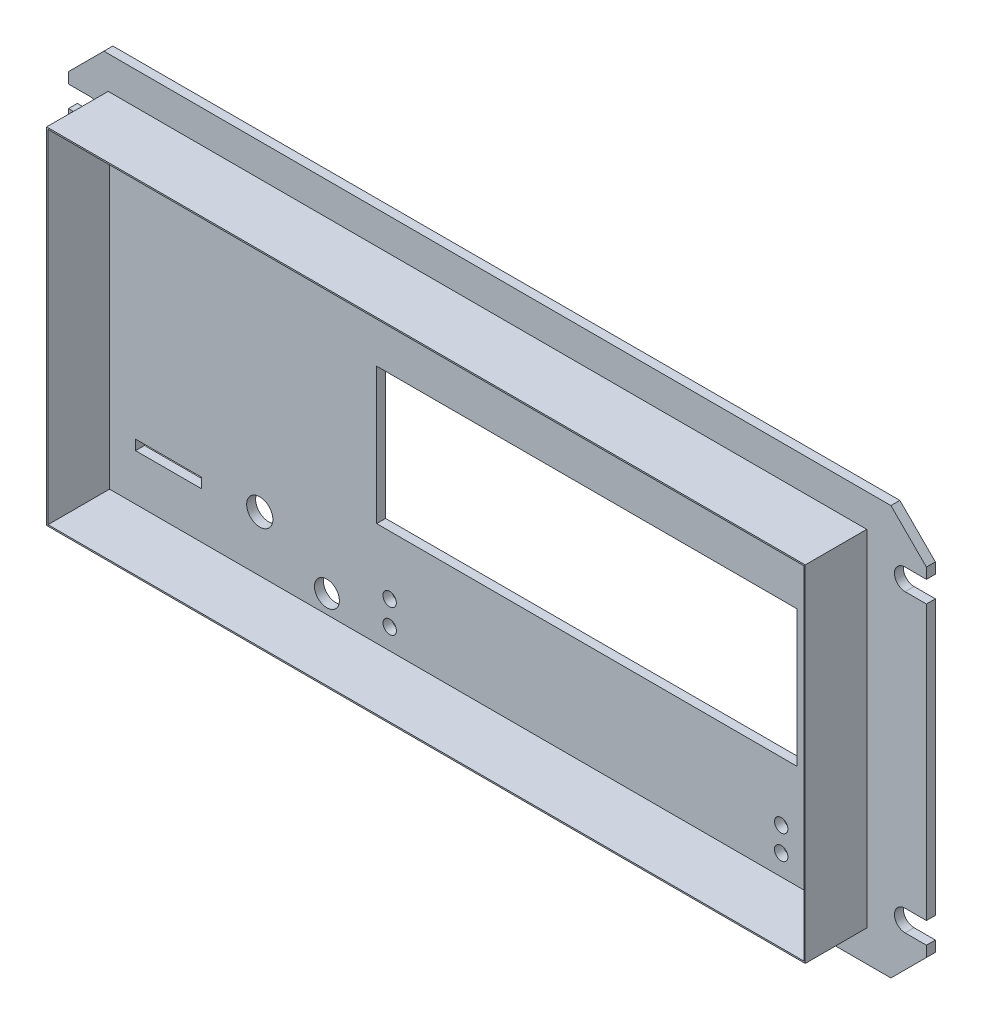
SolidWorks part; units mm, degrees
ref_plane "Front Plane" through (0, 0, 0) normal (0, 0, 1) x (1, 0, 0)
ref_plane "Top Plane" through (0, 0, 0) normal (0, 1, 0) x (1, 0, 0)
ref_plane "Right Plane" through (0, 0, 0) normal (1, 0, 0) x (0, 0, -1)
ref_plane "Plane1" through (0, 0, 1.6002) normal (0, 0, 1) x (1, 0, 0)
sketch "Sketch1" plane through (0, 0, 1.6002) normal (0, 0, 1) x (1, 0, 0)
  line L0 (6.35, 70.612) -> (0, 64.262)
  line L1 (0, 64.262) -> (0, 3.81)
  line L2 (0, 3.81) -> (6.35, -2.54)
  line L3 (6.35, -2.54) -> (147.066, -2.54)
  line L4 (147.066, -2.54) -> (153.416, 3.81)
  line L5 (153.416, 3.81) -> (153.416, 64.262)
  line L6 (153.416, 64.262) -> (147.066, 70.612)
  line L7 (147.066, 70.612) -> (6.35, 70.612)
  dimension "D1" = 153.416
  dimension "D2" = 73.152
  dimension "D3" = 8.9803
  dimension "D4" = 8.9803
  dimension "D5" = 8.9803
  dimension "D6" = 8.9803
  dimension "D7" = 135
  dimension "D8" = 135
  dimension "D9" = 135
  dimension "D10" = 135
  dimension "D11" = 2.54
extrude "Boss-Extrude1" add sketch "Sketch1" against normal blind 1.6002
sketch "Sketch2" plane through (0, 0, 0) normal (0, 0, -1) x (-1, 0, 0)
  line L0 (-153.416, 9.525) -> (-153.416, 5.715)
  line L1 (-153.416, 5.715) -> (-149.606, 5.715)
  line L2 (-149.606, 9.525) -> (-153.416, 9.525)
  arc A0 (-149.606, 5.715) -> (-149.606, 9.525) centre (-149.606, 7.62) ccw
extrude "Cut-Extrude1" cut sketch "Sketch2" against normal through all
sketch "Sketch3" plane through (0, 0, 0) normal (0, 0, -1) x (-1, 0, 0)
  line L0 (-153.416, 62.357) -> (-153.416, 58.547)
  line L1 (-153.416, 58.547) -> (-149.606, 58.547)
  line L2 (-149.606, 62.357) -> (-153.416, 62.357)
  arc A0 (-149.606, 58.547) -> (-149.606, 62.357) centre (-149.606, 60.452) ccw
extrude "Cut-Extrude2" cut sketch "Sketch3" against normal through all
sketch "Sketch4" plane through (0, 0, 0) normal (0, 0, -1) x (-1, 0, 0)
  line L0 (0, 58.547) -> (0, 62.357)
  line L1 (0, 62.357) -> (-3.81, 62.357)
  line L2 (-3.81, 58.547) -> (0, 58.547)
  arc A0 (-3.81, 62.357) -> (-3.81, 58.547) centre (-3.81, 60.452) ccw
extrude "Cut-Extrude3" cut sketch "Sketch4" against normal through all
sketch "Sketch5" plane through (0, 0, 0) normal (0, 0, -1) x (-1, 0, 0)
  line L0 (0, 5.715) -> (0, 9.525)
  line L1 (0, 9.525) -> (-3.81, 9.525)
  line L2 (-3.81, 5.715) -> (0, 5.715)
  arc A0 (-3.81, 9.525) -> (-3.81, 5.715) centre (-3.81, 7.62) ccw
extrude "Cut-Extrude4" cut sketch "Sketch5" against normal through all
sketch "Sketch6" plane through (0, 0, 1.6002) normal (0, 0, 1) x (1, 0, 0)
  line L0 (7.112, 64.77) -> (142.748, 64.77)
  line L1 (142.748, 64.77) -> (142.748, 3.048)
  line L2 (142.748, 3.048) -> (7.112, 3.048)
  line L3 (7.112, 3.048) -> (7.112, 64.77)
extrude "Boss-Extrude2" add sketch "Sketch6" along normal blind 11
sketch "Sketch7" plane through (0, 0, 12.6002) normal (0, 0, 1) x (1, 0, 0)
  line L0 (7.366, 3.302) -> (142.494, 3.302)
  line L1 (142.494, 3.302) -> (142.494, 64.516)
  line L2 (142.494, 64.516) -> (7.366, 64.516)
  line L3 (7.366, 64.516) -> (7.366, 3.302)
extrude "Cut-Extrude5" cut sketch "Sketch7" against normal blind 11
sketch "Sketch8" plane through (0, 0, 1.6002) normal (0, 0, 1) x (1, 0, 0)
  line L0 (55.118, 21.844) -> (130.302, 21.844)
  line L1 (130.302, 21.844) -> (130.302, 46.228)
  line L2 (130.302, 46.228) -> (55.118, 46.228)
  line L3 (55.118, 46.228) -> (55.118, 21.844)
extrude "Cut-Extrude6" cut sketch "Sketch8" against normal through all
sketch "Sketch9" plane through (0, 0, 0) normal (0, 0, -1) x (-1, 0, 0)
  line L0 (-23.8014, 13.3738) -> (-23.8014, 11.5835)
  line L1 (-23.8014, 11.5835) -> (-12.0087, 11.5835)
  line L2 (-12.0087, 11.5835) -> (-12.0087, 13.3738)
  line L3 (-12.0087, 13.3738) -> (-23.8014, 13.3738)
extrude "Cut-Extrude7" cut sketch "Sketch9" against normal through all
hole_wizard "M2 Clearance Hole1" positions "Sketch11" profile "Sketch10" hole size "M2" standard "ANSI Metric"
sketch "Sketch11" plane through (0, 0, 1.6002) normal (0, 0, 1) x (1, 0, 0)
  point P0 (127.4445, 6.9825)
  point P1 (127.4496, 11.303)
  point P2 (57.4548, 7.0333)
  point P3 (57.4396, 11.3233)
sketch "Sketch10" plane through (127.4445, 6.9825, 1.6002) normal (1, 0, 0) x (0, -1, 0)
  line L0 (0, 0) -> (0, 1.6002)
  line L1 (0, 1.6002) -> (1.1989, 1.6002)
  line L2 (1.1989, 1.6002) -> (1.1989, 0)
  line L5 (1.1989, 0) -> (0, 0)
  line L11 (0, -6.35) -> (0, 107.95) construction
  dimension "Thru Hole Dia." = 2.3978
  dimension "Thru Hole Depth" = 1.6002
hole_wizard "M4 Clearance Hole1" positions "Sketch13" profile "Sketch12" hole size "M4" standard "ANSI Metric"
sketch "Sketch13" plane through (0, 0, 1.6002) normal (0, 0, 1) x (1, 0, 0)
  point P0 (46.228, 61.5696)
  point P1 (46.228, 6.5786)
  point P2 (139.2174, 6.5786)
  point P3 (139.2428, 61.5696)
sketch "Sketch12" plane through (46.228, 61.5696, 1.6002) normal (1, 0, 0) x (0, -1, 0)
  line L0 (0, 0) -> (0, 1.6002)
  line L1 (0, 1.6002) -> (2.2225, 1.6002)
  line L2 (2.2225, 1.6002) -> (2.2225, 0)
  line L5 (2.2225, 0) -> (0, 0)
  line L11 (0, -6.35) -> (0, 107.95) construction
  dimension "Thru Hole Dia." = 4.445
  dimension "Thru Hole Depth" = 1.6002
hole_wizard "M4 Clearance Hole2" positions "Sketch15" profile "Sketch14" hole size "M4" standard "ANSI Metric"
sketch "Sketch15" plane through (0, 0, 1.6002) normal (0, 0, 1) x (1, 0, 0)
  point P0 (34.2207, 13.2056)
sketch "Sketch14" plane through (34.2207, 13.2056, 1.6002) normal (1, 0, 0) x (0, -1, 0)
  line L0 (0, 0) -> (0, 1.6002)
  line L1 (0, 1.6002) -> (2.3429, 1.6002)
  line L2 (2.3429, 1.6002) -> (2.3429, 0)
  line L5 (2.3429, 0) -> (0, 0)
  line L11 (0, -6.35) -> (0, 107.95) construction
  dimension "Thru Hole Dia." = 4.6859
  dimension "Thru Hole Depth" = 1.6002
sketch "Sketch18" plane through (0, 0, 0) normal (0, 0, -1) x (-1, 0, 0)
  line L1174 (-76.708, 70.612) -> (-76.708, -2.54) construction
  line L1175 (-12.0087, 11.5835) -> (-23.8014, 11.5835)
  line L1176 (-23.8014, 11.5835) -> (-23.8014, 13.3738)
  line L1177 (-55.118, 21.844) -> (-130.302, 21.844)
  line L1178 (-23.8014, 13.3738) -> (-12.0087, 13.3738)
  line L1179 (-12.0087, 13.3738) -> (-12.0087, 11.5835)
  line L1180 (-55.118, 46.228) -> (-55.118, 21.844)
  line L1209 (-130.302, 46.228) -> (-55.118, 46.228)
  line L1210 (-130.302, 21.844) -> (-130.302, 46.228)
  line L1211 (-149.606, 62.357) -> (-153.416, 62.357)
  line L1212 (-153.416, 5.715) -> (-149.606, 5.715)
  line L1213 (-149.606, 9.525) -> (-153.416, 9.525)
  line L1214 (-6.35, -2.54) -> (-147.066, -2.54)
  line L1215 (0, 3.81) -> (-6.35, -2.54)
  line L1216 (0, 64.262) -> (0, 62.357)
  line L1217 (-6.35, 70.612) -> (0, 64.262)
  line L1218 (-3.81, 5.715) -> (0, 5.715)
  line L1219 (0, 5.715) -> (0, 3.81)
  line L1220 (-147.066, -2.54) -> (-153.416, 3.81)
  line L1221 (-153.416, 3.81) -> (-153.416, 5.715)
  line L1222 (-153.416, 9.525) -> (-153.416, 58.547)
  line L1223 (-153.416, 58.547) -> (-149.606, 58.547)
  line L1224 (-153.416, 62.357) -> (-153.416, 64.262)
  line L1225 (-153.416, 64.262) -> (-147.066, 70.612)
  line L1226 (-147.066, 70.612) -> (-6.35, 70.612)
  line L1227 (0, 62.357) -> (-3.81, 62.357)
  line L1228 (-3.81, 58.547) -> (0, 58.547)
  line L1229 (0, 58.547) -> (0, 9.525)
  line L1230 (0, 9.525) -> (-3.81, 9.525)
  line L1343 (-132.8607, 54.5441) -> (-132.8276, 54.3427)
  line L1344 (-132.9988, 54.754) -> (-132.8607, 54.5441)
  line L1345 (-133.1642, 54.8667) -> (-132.9988, 54.754)
  line L1346 (-133.4172, 54.9182) -> (-133.1642, 54.8667)
  line L1347 (-133.3057, 54.4651) -> (-133.4172, 54.4944)
  line L1348 (-133.2547, 54.3427) -> (-133.3057, 54.4651)
  line L1349 (-133.2862, 53.5711) -> (-133.2547, 53.6753)
  line L1350 (-133.4172, 53.5235) -> (-133.2862, 53.5711)
  line L1351 (-133.2144, 53.1316) -> (-133.4172, 53.0998)
  line L1352 (-132.9988, 53.264) -> (-133.2144, 53.1316)
  line L1353 (-132.8813, 53.4246) -> (-132.9988, 53.264)
  line L1354 (-132.8276, 53.6753) -> (-132.8813, 53.4246)
  line L1355 (-136.5171, 53.5529) -> (-136.4009, 53.5235)
  line L1356 (-136.5703, 53.6753) -> (-136.5171, 53.5529)
  line L1357 (-136.5375, 54.4469) -> (-136.5703, 54.3427)
  line L1358 (-136.4009, 54.4944) -> (-136.5375, 54.4469)
  line L1359 (-136.604, 54.8864) -> (-136.4009, 54.9182)
  line L1360 (-136.8211, 54.754) -> (-136.604, 54.8864)
  line L1361 (-136.9397, 54.5935) -> (-136.8211, 54.754)
  line L1362 (-136.994, 54.3427) -> (-136.9397, 54.5935)
  line L1363 (-136.9605, 53.4739) -> (-136.994, 53.6753)
  line L1364 (-136.8211, 53.264) -> (-136.9605, 53.4739)
  line L1365 (-136.6544, 53.1513) -> (-136.8211, 53.264)
  line L1366 (-136.4009, 53.0998) -> (-136.6544, 53.1513)
  line L1367 (-26.0508, 53.9675) -> (-25.7688, 54.0694)
  line L1368 (-26.2101, 53.628) -> (-26.0508, 53.9675)
  line L1369 (-26.1082, 53.3461) -> (-26.2101, 53.628)
  line L1370 (-25.7688, 53.1868) -> (-26.1082, 53.3461)
  line L1371 (-25.4867, 53.2887) -> (-25.7688, 53.1868)
  line L1372 (-25.3275, 53.628) -> (-25.4867, 53.2887)
  line L1373 (-25.4293, 53.9101) -> (-25.3275, 53.628)
  line L1374 (-25.7688, 54.0694) -> (-25.4293, 53.9101)
  line L1375 (-24.431, 53.9675) -> (-24.1491, 54.0694)
  line L1376 (-24.5903, 53.628) -> (-24.431, 53.9675)
  line L1377 (-24.4884, 53.3461) -> (-24.5903, 53.628)
  line L1378 (-24.1491, 53.1868) -> (-24.4884, 53.3461)
  line L1379 (-23.867, 53.2887) -> (-24.1491, 53.1868)
  line L1380 (-23.7077, 53.628) -> (-23.867, 53.2887)
  line L1381 (-23.8096, 53.9101) -> (-23.7077, 53.628)
  line L1382 (-24.1491, 54.0694) -> (-23.8096, 53.9101)
  line L1383 (-27.6706, 53.9675) -> (-27.3885, 54.0694)
  line L1384 (-27.8298, 53.628) -> (-27.6706, 53.9675)
  line L1385 (-27.728, 53.3461) -> (-27.8298, 53.628)
  line L1386 (-27.3885, 53.1868) -> (-27.728, 53.3461)
  line L1387 (-27.1065, 53.2887) -> (-27.3885, 53.1868)
  line L1388 (-26.9472, 53.628) -> (-27.1065, 53.2887)
  line L1389 (-27.0491, 53.9101) -> (-26.9472, 53.628)
  line L1390 (-27.3885, 54.0694) -> (-27.0491, 53.9101)
  line L1391 (-11.8759, 8.1379) -> (-11.8527, 7.9968)
  line L1392 (-11.9725, 8.2848) -> (-11.8759, 8.1379)
  line L1393 (-12.0883, 8.3637) -> (-11.9725, 8.2848)
  line L1394 (-12.2654, 8.3997) -> (-12.0883, 8.3637)
  line L1395 (-12.1874, 8.0826) -> (-12.2654, 8.1032)
  line L1396 (-12.1518, 7.9968) -> (-12.1874, 8.0826)
  line L1397 (-12.1738, 7.4568) -> (-12.1518, 7.5297)
  line L1398 (-12.2654, 7.4235) -> (-12.1738, 7.4568)
  line L1399 (-12.1235, 7.1491) -> (-12.2654, 7.1268)
  line L1400 (-11.9725, 7.2418) -> (-12.1235, 7.1491)
  line L1401 (-11.8903, 7.3542) -> (-11.9725, 7.2418)
  line L1402 (-11.8527, 7.5297) -> (-11.8903, 7.3542)
  line L1403 (-13.3889, 7.6521) -> (-13.3703, 7.5198)
  line L1404 (-13.4666, 7.7942) -> (-13.3889, 7.6521)
  line L1405 (-13.5685, 7.8757) -> (-13.4666, 7.7942)
  line L1406 (-13.7286, 7.9129) -> (-13.5685, 7.8757)
  line L1407 (-14.5694, 7.9311) -> (-14.527, 7.9129)
  line L1408 (-14.5888, 8.0068) -> (-14.5694, 7.9311)
  line L1409 (-14.5768, 8.0729) -> (-14.5888, 8.0068)
  line L1410 (-14.527, 8.1032) -> (-14.5768, 8.0729)
  line L1411 (-14.6552, 8.3773) -> (-14.527, 8.3997)
  line L1412 (-14.7865, 8.2837) -> (-14.6552, 8.3773)
  line L1413 (-14.856, 8.1728) -> (-14.7865, 8.2837)
  line L1414 (-14.8878, 8.0068) -> (-14.856, 8.1728)
  line L1415 (-14.8687, 7.875) -> (-14.8878, 8.0068)
  line L1416 (-14.7889, 7.7349) -> (-14.8687, 7.875)
  line L1417 (-14.6871, 7.6535) -> (-14.7889, 7.7349)
  line L1418 (-14.527, 7.6162) -> (-14.6871, 7.6535)
  line L1419 (-13.6863, 7.5975) -> (-13.7286, 7.6162)
  line L1420 (-13.6669, 7.5198) -> (-13.6863, 7.5975)
  line L1421 (-13.6789, 7.4537) -> (-13.6669, 7.5198)
  line L1422 (-13.7286, 7.4235) -> (-13.6789, 7.4537)
  line L1423 (-13.5999, 7.1498) -> (-13.7286, 7.1268)
  line L1424 (-13.4666, 7.2455) -> (-13.5999, 7.1498)
  line L1425 (-13.4005, 7.3547) -> (-13.4666, 7.2455)
  line L1426 (-13.3703, 7.5198) -> (-13.4005, 7.3547)
  line L1427 (-15.3308, 7.4568) -> (-15.3079, 7.5297)
  line L1428 (-15.4266, 7.4235) -> (-15.3308, 7.4568)
  line L1429 (-16.2545, 7.444) -> (-16.173, 7.4235)
  line L1430 (-16.2918, 7.5297) -> (-16.2545, 7.444)
  line L1431 (-16.2688, 8.0698) -> (-16.2918, 7.9968)
  line L1432 (-16.173, 8.1032) -> (-16.2688, 8.0698)
  line L1433 (-15.3451, 8.0826) -> (-15.4266, 8.1032)
  line L1434 (-15.3079, 7.9968) -> (-15.3451, 8.0826)
  line L1435 (-15.0348, 8.1379) -> (-15.0113, 7.9968)
  line L1436 (-15.1324, 8.2848) -> (-15.0348, 8.1379)
  line L1437 (-15.2491, 8.3637) -> (-15.1324, 8.2848)
  line L1438 (-15.4266, 8.3997) -> (-15.2491, 8.3637)
  line L1439 (-16.3152, 8.3775) -> (-16.173, 8.3997)
  line L1440 (-16.4672, 8.2848) -> (-16.3152, 8.3775)
  line L1441 (-16.5503, 8.1724) -> (-16.4672, 8.2848)
  line L1442 (-16.5882, 7.9968) -> (-16.5503, 8.1724)
  line L1443 (-16.5648, 7.3888) -> (-16.5882, 7.5297)
  line L1444 (-16.4672, 7.2418) -> (-16.5648, 7.3888)
  line L1445 (-16.3505, 7.1629) -> (-16.4672, 7.2418)
  line L1446 (-16.173, 7.1268) -> (-16.3505, 7.1629)
  line L1447 (-15.2844, 7.1491) -> (-15.4266, 7.1268)
  line L1448 (-15.1324, 7.2418) -> (-15.2844, 7.1491)
  line L1449 (-15.0493, 7.3542) -> (-15.1324, 7.2418)
  line L1450 (-15.0113, 7.5297) -> (-15.0493, 7.3542)
  line L1451 (-16.9364, 7.5704) -> (-17.0726, 7.5446)
  line L1452 (-16.8032, 7.678) -> (-16.9364, 7.5704)
  line L1453 (-16.7405, 7.7947) -> (-16.8032, 7.678)
  line L1454 (-16.7118, 7.9722) -> (-16.7405, 7.7947)
  line L1455 (-16.7295, 8.1144) -> (-16.7118, 7.9722)
  line L1456 (-16.8032, 8.2663) -> (-16.7295, 8.1144)
  line L1457 (-16.9041, 8.3579) -> (-16.8032, 8.2663)
  line L1458 (-17.0726, 8.3997) -> (-16.9041, 8.3579)
  line L1459 (-17.0542, 8.095) -> (-17.0899, 8.1032)
  line L1460 (-17.0288, 8.0704) -> (-17.0542, 8.095)
  line L1461 (-17.0085, 7.9722) -> (-17.0288, 8.0704)
  line L1462 (-17.0288, 7.8739) -> (-17.0085, 7.9722)
  line L1463 (-17.0542, 7.8494) -> (-17.0288, 7.8739)
  line L1464 (-17.0899, 7.8412) -> (-17.0542, 7.8494)
  line L1465 (-19.4948, 7.444) -> (-19.4132, 7.4235)
  line L1466 (-19.532, 7.5297) -> (-19.4948, 7.444)
  line L1467 (-19.509, 8.0698) -> (-19.532, 7.9968)
  line L1468 (-19.4132, 8.1032) -> (-19.509, 8.0698)
  line L1469 (-19.5555, 8.3775) -> (-19.4132, 8.3997)
  line L1470 (-19.7075, 8.2848) -> (-19.5555, 8.3775)
  line L1471 (-19.7906, 8.1724) -> (-19.7075, 8.2848)
  line L1472 (-19.8286, 7.9968) -> (-19.7906, 8.1724)
  line L1473 (-19.8051, 7.3888) -> (-19.8286, 7.5297)
  line L1474 (-19.7075, 7.2418) -> (-19.8051, 7.3888)
  line L1475 (-19.5908, 7.1629) -> (-19.7075, 7.2418)
  line L1476 (-19.4132, 7.1268) -> (-19.5908, 7.1629)
  line L1477 (-68.5411, 10.185) -> (-67.1131, 9.6692)
  line L1478 (-69.3477, 11.9041) -> (-68.5411, 10.185)
  line L1479 (-68.8319, 13.3321) -> (-69.3477, 11.9041)
  line L1480 (-67.1131, 14.1387) -> (-68.8319, 13.3321)
  line L1481 (-65.685, 13.6229) -> (-67.1131, 14.1387)
  line L1482 (-64.8784, 11.9041) -> (-65.685, 13.6229)
  line L1483 (-65.3941, 10.4759) -> (-64.8784, 11.9041)
  line L1484 (-67.1131, 9.6692) -> (-65.3941, 10.4759)
  line L1485 (-66.9969, 12.081) -> (-67.1639, 12.1014)
  line L1486 (-66.9124, 11.9557) -> (-66.9969, 12.081)
  line L1487 (-66.9254, 11.8036) -> (-66.9124, 11.9557)
  line L1488 (-67.0514, 11.703) -> (-66.9254, 11.8036)
  line L1489 (-67.2229, 11.7242) -> (-67.0514, 11.703)
  line L1490 (-67.3137, 11.8458) -> (-67.2229, 11.7242)
  line L1491 (-67.3016, 11.9956) -> (-67.3137, 11.8458)
  line L1492 (-67.1639, 12.1014) -> (-67.3016, 11.9956)
  line L1493 (-66.8677, 11.7329) -> (-66.9688, 11.6386)
  line L1494 (-66.8123, 11.9269) -> (-66.8677, 11.7329)
  line L1495 (-66.3706, 11.7784) -> (-66.8123, 11.9269)
  line L1496 (-65.8217, 11.6381) -> (-66.3706, 11.7784)
  line L1497 (-65.5275, 11.4963) -> (-65.8217, 11.6381)
  line L1498 (-65.3974, 11.2871) -> (-65.5275, 11.4963)
  line L1499 (-65.4879, 10.8793) -> (-65.3974, 11.2871)
  line L1500 (-65.7155, 10.7223) -> (-65.4879, 10.8793)
  line L1501 (-65.9453, 10.7264) -> (-65.7155, 10.7223)
  line L1502 (-66.3558, 10.9747) -> (-65.9453, 10.7264)
  line L1503 (-67.3728, 12.607) -> (-67.2922, 12.1626)
  line L1504 (-67.5242, 13.1362) -> (-67.3728, 12.607)
  line L1505 (-67.5042, 13.6117) -> (-67.5242, 13.1362)
  line L1506 (-67.0788, 13.8266) -> (-67.5042, 13.6117)
  line L1507 (-66.8272, 13.7425) -> (-67.0788, 13.8266)
  line L1508 (-66.6992, 13.5602) -> (-66.8272, 13.7425)
  line L1509 (-66.6825, 13.0699) -> (-66.6992, 13.5602)
  line L1510 (-67.5497, 11.3697) -> (-67.2445, 11.6171)
  line L1511 (-67.9168, 10.9958) -> (-67.5497, 11.3697)
  line L1512 (-68.0452, 10.8548) -> (-67.9168, 10.9958)
  line L1513 (-68.2885, 10.7208) -> (-68.0452, 10.8548)
  line L1514 (-68.6617, 11.5341) -> (-68.7887, 11.3865)
  line L1515 (-68.4305, 11.6571) -> (-68.6617, 11.5341)
  line L1516 (-68.01, 11.8007) -> (-68.4305, 11.6571)
  line L1517 (-67.4152, 11.9161) -> (-68.01, 11.8007)
  line L1518 (-29.4673, 7.2241) -> (-29.2354, 7.8662)
  line L1519 (-30.2404, 6.8614) -> (-29.4673, 7.2241)
  line L1520 (-30.8825, 7.0933) -> (-30.2404, 6.8614)
  line L1521 (-31.2453, 7.8662) -> (-30.8825, 7.0933)
  line L1522 (-31.0133, 8.5085) -> (-31.2453, 7.8662)
  line L1523 (-30.2404, 8.8713) -> (-31.0133, 8.5085)
  line L1524 (-54.4852, 10.6159) -> (-53.4697, 10.2491)
  line L1525 (-55.0586, 11.8381) -> (-54.4852, 10.6159)
  line L1526 (-54.6919, 12.8535) -> (-55.0586, 11.8381)
  line L1527 (-53.4697, 13.4271) -> (-54.6919, 12.8535)
  line L1528 (-52.4543, 13.0603) -> (-53.4697, 13.4271)
  line L1529 (-51.8808, 11.8381) -> (-52.4543, 13.0603)
  line L1530 (-52.2475, 10.8227) -> (-51.8808, 11.8381)
  line L1531 (-53.4697, 10.2491) -> (-52.2475, 10.8227)
  line L1532 (-53.9743, 11.4422) -> (-53.8696, 11.4157)
  line L1533 (-54.0222, 11.5523) -> (-53.9743, 11.4422)
  line L1534 (-53.9926, 12.2468) -> (-54.0222, 12.153)
  line L1535 (-53.8696, 12.2896) -> (-53.9926, 12.2468)
  line L1536 (-54.0524, 12.6423) -> (-53.8696, 12.6709)
  line L1537 (-54.2477, 12.5233) -> (-54.0524, 12.6423)
  line L1538 (-54.3546, 12.3788) -> (-54.2477, 12.5233)
  line L1539 (-54.4034, 12.153) -> (-54.3546, 12.3788)
  line L1540 (-54.3733, 11.3711) -> (-54.4034, 11.5523)
  line L1541 (-54.2477, 11.182) -> (-54.3733, 11.3711)
  line L1542 (-54.0978, 11.0807) -> (-54.2477, 11.182)
  line L1543 (-53.8696, 11.0344) -> (-54.0978, 11.0807)
  line L1544 (-132.5876, 6.2753) -> (-131.5722, 5.9085)
  line L1545 (-133.1611, 7.4976) -> (-132.5876, 6.2753)
  line L1546 (-132.7944, 8.5129) -> (-133.1611, 7.4976)
  line L1547 (-131.5722, 9.0865) -> (-132.7944, 8.5129)
  line L1548 (-130.5567, 8.7197) -> (-131.5722, 9.0865)
  line L1549 (-129.9832, 7.4976) -> (-130.5567, 8.7197)
  line L1550 (-130.3499, 6.4821) -> (-129.9832, 7.4976)
  line L1551 (-131.5722, 5.9085) -> (-130.3499, 6.4821)
  line L1552 (-130.8634, 7.299) -> (-130.9201, 7.323)
  line L1553 (-130.8375, 7.199) -> (-130.8634, 7.299)
  line L1554 (-130.8535, 7.114) -> (-130.8375, 7.199)
  line L1555 (-130.9201, 7.0751) -> (-130.8535, 7.114)
  line L1556 (-130.892, 7.925) -> (-130.9487, 7.949)
  line L1557 (-130.8661, 7.8251) -> (-130.892, 7.925)
  line L1558 (-130.8821, 7.7401) -> (-130.8661, 7.8251)
  line L1559 (-130.9487, 7.7012) -> (-130.8821, 7.7401)
  line L1560 (-130.5439, 7.6547) -> (-130.6595, 7.5232)
  line L1561 (-130.491, 7.8792) -> (-130.5439, 7.6547)
  line L1562 (-130.5132, 8.0303) -> (-130.491, 7.8792)
  line L1563 (-130.6055, 8.1906) -> (-130.5132, 8.0303)
  line L1564 (-130.7346, 8.2865) -> (-130.6055, 8.1906)
  line L1565 (-130.9487, 8.3303) -> (-130.7346, 8.2865)
  line L1566 (-130.7472, 6.7209) -> (-130.9201, 6.6938)
  line L1567 (-130.5768, 6.8336) -> (-130.7472, 6.7209)
  line L1568 (-130.4962, 6.9565) -> (-130.5768, 6.8336)
  line L1569 (-130.4593, 7.1451) -> (-130.4962, 6.9565)
  line L1570 (-130.498, 7.3435) -> (-130.4593, 7.1451)
  line L1571 (-130.6595, 7.5232) -> (-130.498, 7.3435)
  line L1572 (-132.5189, 10.7035) -> (-131.5035, 10.3368)
  line L1573 (-133.0924, 11.9258) -> (-132.5189, 10.7035)
  line L1574 (-132.7257, 12.9412) -> (-133.0924, 11.9258)
  line L1575 (-131.5035, 13.5147) -> (-132.7257, 12.9412)
  line L1576 (-130.488, 13.148) -> (-131.5035, 13.5147)
  line L1577 (-129.9145, 11.9258) -> (-130.488, 13.148)
  line L1578 (-130.2812, 10.9103) -> (-129.9145, 11.9258)
  line L1579 (-131.5035, 10.3368) -> (-130.2812, 10.9103)
  line L1580 (-121.9015, 12.9336) -> (-122.3691, 12.2681)
  line L1581 (-122.3691, 13.7805) -> (-121.9015, 12.9336)
  line L1582 (-122.8368, 11.6027) -> (-122.3691, 12.2681)
  line L1583 (-122.3691, 10.7557) -> (-122.8368, 11.6027)
  line L1584 (-122.6735, 12.9336) -> (-123.1411, 12.2681)
  line L1585 (-123.1411, 13.7805) -> (-122.6735, 12.9336)
  line L1586 (-123.6088, 11.6027) -> (-123.1411, 12.2681)
  line L1587 (-123.1411, 10.7557) -> (-123.6088, 11.6027)
  line L1588 (-123.4438, 12.9336) -> (-123.9114, 12.2681)
  line L1589 (-123.9114, 13.7805) -> (-123.4438, 12.9336)
  line L1590 (-124.3791, 11.6027) -> (-123.9114, 12.2681)
  line L1591 (-123.9114, 10.7557) -> (-124.3791, 11.6027)
  line L1592 (-124.2158, 12.9336) -> (-124.6834, 12.2681)
  line L1593 (-124.6834, 13.7805) -> (-124.2158, 12.9336)
  line L1594 (-125.151, 11.6027) -> (-124.6834, 12.2681)
  line L1595 (-124.6834, 10.7557) -> (-125.151, 11.6027)
  line L1596 (-51.4709, 7.9134) -> (-51.4411, 7.7321)
  line L1597 (-51.5952, 8.1024) -> (-51.4709, 7.9134)
  line L1598 (-51.744, 8.2038) -> (-51.5952, 8.1024)
  line L1599 (-51.9716, 8.2501) -> (-51.744, 8.2038)
  line L1600 (-51.8713, 7.8423) -> (-51.9716, 7.8687)
  line L1601 (-51.8255, 7.7321) -> (-51.8713, 7.8423)
  line L1602 (-51.8538, 7.0377) -> (-51.8255, 7.1314)
  line L1603 (-51.9716, 6.9948) -> (-51.8538, 7.0377)
  line L1604 (-51.7892, 6.6422) -> (-51.9716, 6.6136)
  line L1605 (-51.5952, 6.7613) -> (-51.7892, 6.6422)
  line L1606 (-51.4894, 6.9058) -> (-51.5952, 6.7613)
  line L1607 (-51.4411, 7.1314) -> (-51.4894, 6.9058)
  line L1608 (-53.4162, 7.2889) -> (-53.3922, 7.1188)
  line L1609 (-53.516, 7.4716) -> (-53.4162, 7.2889)
  line L1610 (-53.6471, 7.5763) -> (-53.516, 7.4716)
  line L1611 (-53.8531, 7.6242) -> (-53.6471, 7.5763)
  line L1612 (-54.9339, 7.6475) -> (-54.8794, 7.6242)
  line L1613 (-54.9589, 7.7448) -> (-54.9339, 7.6475)
  line L1614 (-54.9435, 7.8299) -> (-54.9589, 7.7448)
  line L1615 (-54.8794, 7.8687) -> (-54.9435, 7.8299)
  line L1616 (-55.0442, 8.2212) -> (-54.8794, 8.2501)
  line L1617 (-55.2132, 8.1007) -> (-55.0442, 8.2212)
  line L1618 (-55.3026, 7.9582) -> (-55.2132, 8.1007)
  line L1619 (-55.3435, 7.7448) -> (-55.3026, 7.9582)
  line L1620 (-55.3188, 7.5754) -> (-55.3435, 7.7448)
  line L1621 (-55.2163, 7.3954) -> (-55.3188, 7.5754)
  line L1622 (-55.0853, 7.2906) -> (-55.2163, 7.3954)
  line L1623 (-54.8794, 7.2428) -> (-55.0853, 7.2906)
  line L1624 (-53.7985, 7.2187) -> (-53.8531, 7.2428)
  line L1625 (-53.7736, 7.1188) -> (-53.7985, 7.2187)
  line L1626 (-53.789, 7.0337) -> (-53.7736, 7.1188)
  line L1627 (-53.8531, 6.9948) -> (-53.789, 7.0337)
  line L1628 (-53.6875, 6.6431) -> (-53.8531, 6.6136)
  line L1629 (-53.516, 6.766) -> (-53.6875, 6.6431)
  line L1630 (-53.431, 6.9063) -> (-53.516, 6.766)
  line L1631 (-53.3922, 7.1188) -> (-53.431, 6.9063)
  line L1632 (-130.5255, 12.4095) -> (-130.5006, 12.2388)
  line L1633 (-130.6293, 12.5947) -> (-130.5255, 12.4095)
  line L1634 (-130.7577, 12.6972) -> (-130.6293, 12.5947)
  line L1635 (-130.9646, 12.744) -> (-130.7577, 12.6972)
  line L1636 (-132.2096, 12.7151) -> (-132.0451, 12.744)
  line L1637 (-132.3771, 12.5947) -> (-132.2096, 12.7151)
  line L1638 (-132.4655, 12.4522) -> (-132.3771, 12.5947)
  line L1639 (-132.5059, 12.2388) -> (-132.4655, 12.4522)
  line L1640 (-132.1092, 12.3238) -> (-132.1246, 12.2388)
  line L1641 (-132.0451, 12.3627) -> (-132.1092, 12.3238)
  line L1642 (-130.9079, 12.3387) -> (-130.9646, 12.3627)
  line L1643 (-130.8819, 12.2388) -> (-130.9079, 12.3387)
  line L1644 (-9.2125, 3.2454) -> (-9.1958, 3.1616)
  line L1645 (-9.2819, 3.3386) -> (-9.2125, 3.2454)
  line L1646 (-9.3643, 3.3913) -> (-9.2819, 3.3386)
  line L1647 (-9.4879, 3.4154) -> (-9.3643, 3.3913)
  line L1648 (-9.9067, 3.4191) -> (-9.8814, 3.4154)
  line L1649 (-9.9347, 3.4346) -> (-9.9067, 3.4191)
  line L1650 (-9.9501, 3.4526) -> (-9.9347, 3.4346)
  line L1651 (-9.9571, 3.479) -> (-9.9501, 3.4526)
  line L1652 (-9.9528, 3.5) -> (-9.9571, 3.479)
  line L1653 (-9.9347, 3.5231) -> (-9.9528, 3.5)
  line L1654 (-9.9131, 3.5363) -> (-9.9347, 3.5231)
  line L1655 (-9.8814, 3.5423) -> (-9.9131, 3.5363)
  line L1656 (-10.018, 3.7387) -> (-9.9192, 3.7536)
  line L1657 (-10.1251, 3.6768) -> (-10.018, 3.7387)
  line L1658 (-10.1842, 3.6051) -> (-10.1251, 3.6768)
  line L1659 (-10.2112, 3.5001) -> (-10.1842, 3.6051)
  line L1660 (-10.1945, 3.4164) -> (-10.2112, 3.5001)
  line L1661 (-10.1251, 3.3228) -> (-10.1945, 3.4164)
  line L1662 (-10.0427, 3.2701) -> (-10.1251, 3.3228)
  line L1663 (-9.9192, 3.246) -> (-10.0427, 3.2701)
  line L1664 (-9.5004, 3.2423) -> (-9.5257, 3.246)
  line L1665 (-9.4724, 3.2268) -> (-9.5004, 3.2423)
  line L1666 (-9.4566, 3.2091) -> (-9.4724, 3.2268)
  line L1667 (-9.4493, 3.1827) -> (-9.4566, 3.2091)
  line L1668 (-9.4538, 3.1616) -> (-9.4493, 3.1827)
  line L1669 (-9.4724, 3.1381) -> (-9.4538, 3.1616)
  line L1670 (-9.4939, 3.1249) -> (-9.4724, 3.1381)
  line L1671 (-9.5257, 3.1189) -> (-9.4939, 3.1249)
  line L1672 (-9.3894, 2.9222) -> (-9.4879, 2.9075)
  line L1673 (-9.2819, 2.9837) -> (-9.3894, 2.9222)
  line L1674 (-9.2228, 3.0561) -> (-9.2819, 2.9837)
  line L1675 (-9.1958, 3.1616) -> (-9.2228, 3.0561)
  line L1676 (-11.6762, 3.123) -> (-11.6462, 3.1189)
  line L1677 (-11.7094, 3.1407) -> (-11.6762, 3.123)
  line L1678 (-11.7269, 3.1615) -> (-11.7094, 3.1407)
  line L1679 (-11.7348, 3.1934) -> (-11.7269, 3.1615)
  line L1680 (-11.7299, 3.4935) -> (-11.7348, 3.4684)
  line L1681 (-11.7094, 3.5205) -> (-11.7299, 3.4935)
  line L1682 (-11.6838, 3.5355) -> (-11.7094, 3.5205)
  line L1683 (-11.6462, 3.5423) -> (-11.6838, 3.5355)
  line L1684 (-11.7798, 3.7385) -> (-11.6716, 3.7536)
  line L1685 (-11.8961, 3.6755) -> (-11.7798, 3.7385)
  line L1686 (-11.9599, 3.6014) -> (-11.8961, 3.6755)
  line L1687 (-11.9889, 3.4896) -> (-11.9599, 3.6014)
  line L1688 (-11.971, 3.0821) -> (-11.9889, 3.1722)
  line L1689 (-11.8961, 2.9849) -> (-11.971, 3.0821)
  line L1690 (-11.8061, 2.9318) -> (-11.8961, 2.9849)
  line L1691 (-11.6716, 2.9075) -> (-11.8061, 2.9318)
  line L1692 (-14.4437, 3.1675) -> (-14.4387, 3.1934)
  line L1693 (-14.4648, 3.1407) -> (-14.4437, 3.1675)
  line L1694 (-14.4905, 3.1257) -> (-14.4648, 3.1407)
  line L1695 (-14.528, 3.1189) -> (-14.4905, 3.1257)
  line L1696 (-14.4981, 3.5381) -> (-14.528, 3.5423)
  line L1697 (-14.4648, 3.5205) -> (-14.4981, 3.5381)
  line L1698 (-14.4469, 3.4997) -> (-14.4648, 3.5205)
  line L1699 (-14.4387, 3.4684) -> (-14.4469, 3.4997)
  line L1700 (-14.2032, 3.5791) -> (-14.1852, 3.4896)
  line L1701 (-14.2781, 3.6755) -> (-14.2032, 3.5791)
  line L1702 (-14.3674, 3.7291) -> (-14.2781, 3.6755)
  line L1703 (-14.5026, 3.7536) -> (-14.3674, 3.7291)
  line L1704 (-14.395, 2.9225) -> (-14.5026, 2.9075)
  line L1705 (-14.2781, 2.9849) -> (-14.395, 2.9225)
  line L1706 (-14.2144, 3.0597) -> (-14.2781, 2.9849)
  line L1707 (-14.1852, 3.1722) -> (-14.2144, 3.0597)
  line L1708 (-18.1338, 3.1226) -> (-18.1085, 3.1189)
  line L1709 (-18.1619, 3.1381) -> (-18.1338, 3.1226)
  line L1710 (-18.1771, 3.1562) -> (-18.1619, 3.1381)
  line L1711 (-18.184, 3.1827) -> (-18.1771, 3.1562)
  line L1712 (-18.1797, 3.2038) -> (-18.184, 3.1827)
  line L1713 (-18.1619, 3.2268) -> (-18.1797, 3.2038)
  line L1714 (-18.1402, 3.24) -> (-18.1619, 3.2268)
  line L1715 (-18.1085, 3.246) -> (-18.1402, 3.24)
  line L1716 (-17.4409, 3.5791) -> (-17.4229, 3.4896)
  line L1717 (-17.5158, 3.6755) -> (-17.4409, 3.5791)
  line L1718 (-17.6051, 3.7291) -> (-17.5158, 3.6755)
  line L1719 (-17.7403, 3.7536) -> (-17.6051, 3.7291)
  line L1720 (-17.7274, 3.5386) -> (-17.7526, 3.5423)
  line L1721 (-17.6993, 3.5231) -> (-17.7274, 3.5386)
  line L1722 (-17.6836, 3.5054) -> (-17.6993, 3.5231)
  line L1723 (-17.6765, 3.479) -> (-17.6836, 3.5054)
  line L1724 (-18.2451, 3.4005) -> (-18.1463, 3.4154)
  line L1725 (-18.352, 3.3386) -> (-18.2451, 3.4005)
  line L1726 (-18.4113, 3.2666) -> (-18.352, 3.3386)
  line L1727 (-18.4384, 3.1616) -> (-18.4113, 3.2666)
  line L1728 (-18.4217, 3.0774) -> (-18.4384, 3.1616)
  line L1729 (-18.352, 2.9837) -> (-18.4217, 3.0774)
  line L1730 (-18.2698, 2.9314) -> (-18.352, 2.9837)
  line L1731 (-18.1463, 2.9075) -> (-18.2698, 2.9314)
  line L1732 (-19.0144, 3.123) -> (-18.9844, 3.1189)
  line L1733 (-19.0477, 3.1407) -> (-19.0144, 3.123)
  line L1734 (-19.0651, 3.1615) -> (-19.0477, 3.1407)
  line L1735 (-19.0731, 3.1934) -> (-19.0651, 3.1615)
  line L1736 (-19.0681, 3.4935) -> (-19.0731, 3.4684)
  line L1737 (-19.0477, 3.5205) -> (-19.0681, 3.4935)
  line L1738 (-19.022, 3.5355) -> (-19.0477, 3.5205)
  line L1739 (-18.9844, 3.5423) -> (-19.022, 3.5355)
  line L1740 (-19.118, 3.7385) -> (-19.0098, 3.7536)
  line L1741 (-19.2343, 3.6755) -> (-19.118, 3.7385)
  line L1742 (-19.2981, 3.6014) -> (-19.2343, 3.6755)
  line L1743 (-19.3272, 3.4896) -> (-19.2981, 3.6014)
  line L1744 (-19.3093, 3.0821) -> (-19.3272, 3.1722)
  line L1745 (-19.2343, 2.9849) -> (-19.3093, 3.0821)
  line L1746 (-19.1444, 2.9318) -> (-19.2343, 2.9849)
  line L1747 (-19.0098, 2.9075) -> (-19.1444, 2.9318)
  line L1748 (-19.5857, 3.1675) -> (-19.5807, 3.1934)
  line L1749 (-19.6068, 3.1407) -> (-19.5857, 3.1675)
  line L1750 (-19.6325, 3.1257) -> (-19.6068, 3.1407)
  line L1751 (-19.67, 3.1189) -> (-19.6325, 3.1257)
  line L1752 (-20.0297, 3.123) -> (-19.9996, 3.1189)
  line L1753 (-20.0629, 3.1407) -> (-20.0297, 3.123)
  line L1754 (-20.0804, 3.1615) -> (-20.0629, 3.1407)
  line L1755 (-20.0883, 3.1934) -> (-20.0804, 3.1615)
  line L1756 (-20.3246, 3.0821) -> (-20.3427, 3.1722)
  line L1757 (-20.2496, 2.9849) -> (-20.3246, 3.0821)
  line L1758 (-20.1597, 2.9318) -> (-20.2496, 2.9849)
  line L1759 (-20.0253, 2.9075) -> (-20.1597, 2.9318)
  line L1760 (-19.537, 2.9225) -> (-19.6446, 2.9075)
  line L1761 (-19.4201, 2.9849) -> (-19.537, 2.9225)
  line L1762 (-19.3563, 3.0597) -> (-19.4201, 2.9849)
  line L1763 (-19.3272, 3.1722) -> (-19.3563, 3.0597)
  line L1764 (-20.3606, 3.5791) -> (-20.3427, 3.4896)
  line L1765 (-20.4356, 3.6755) -> (-20.3606, 3.5791)
  line L1766 (-20.5248, 3.7291) -> (-20.4356, 3.6755)
  line L1767 (-20.66, 3.7536) -> (-20.5248, 3.7291)
  line L1768 (-20.6555, 3.5381) -> (-20.6854, 3.5423)
  line L1769 (-20.6222, 3.5205) -> (-20.6555, 3.5381)
  line L1770 (-20.6043, 3.4997) -> (-20.6222, 3.5205)
  line L1771 (-20.5961, 3.4684) -> (-20.6043, 3.4997)
  line L1772 (-22.069, 3.1226) -> (-22.0437, 3.1189)
  line L1773 (-22.097, 3.1381) -> (-22.069, 3.1226)
  line L1774 (-22.1122, 3.1562) -> (-22.097, 3.1381)
  line L1775 (-22.1192, 3.1827) -> (-22.1122, 3.1562)
  line L1776 (-22.1149, 3.2038) -> (-22.1192, 3.1827)
  line L1777 (-22.097, 3.2268) -> (-22.1149, 3.2038)
  line L1778 (-22.0754, 3.24) -> (-22.097, 3.2268)
  line L1779 (-22.0437, 3.246) -> (-22.0754, 3.24)
  line L1780 (-21.376, 3.5791) -> (-21.358, 3.4896)
  line L1781 (-21.451, 3.6755) -> (-21.376, 3.5791)
  line L1782 (-21.5403, 3.7291) -> (-21.451, 3.6755)
  line L1783 (-21.6754, 3.7536) -> (-21.5403, 3.7291)
  line L1784 (-21.6626, 3.5386) -> (-21.6877, 3.5423)
  line L1785 (-21.6344, 3.5231) -> (-21.6626, 3.5386)
  line L1786 (-21.6188, 3.5054) -> (-21.6344, 3.5231)
  line L1787 (-21.6116, 3.479) -> (-21.6188, 3.5054)
  line L1788 (-22.1804, 3.4005) -> (-22.0816, 3.4154)
  line L1789 (-22.2873, 3.3386) -> (-22.1804, 3.4005)
  line L1790 (-22.3464, 3.2666) -> (-22.2873, 3.3386)
  line L1791 (-22.3735, 3.1616) -> (-22.3464, 3.2666)
  line L1792 (-22.3568, 3.0774) -> (-22.3735, 3.1616)
  line L1793 (-22.2873, 2.9837) -> (-22.3568, 3.0774)
  line L1794 (-22.205, 2.9314) -> (-22.2873, 2.9837)
  line L1795 (-22.0816, 2.9075) -> (-22.205, 2.9314)
  line L1796 (-22.6321, 3.3793) -> (-22.627, 3.4047)
  line L1797 (-22.653, 3.3527) -> (-22.6321, 3.3793)
  line L1798 (-22.6788, 3.3377) -> (-22.653, 3.3527)
  line L1799 (-22.7163, 3.3309) -> (-22.6788, 3.3377)
  line L1800 (-22.6864, 3.5381) -> (-22.7163, 3.5423)
  line L1801 (-22.653, 3.5205) -> (-22.6864, 3.5381)
  line L1802 (-22.6352, 3.4997) -> (-22.653, 3.5205)
  line L1803 (-22.627, 3.4684) -> (-22.6352, 3.4997)
  line L1804 (-22.3915, 3.5791) -> (-22.3735, 3.4896)
  line L1805 (-22.4664, 3.6755) -> (-22.3915, 3.5791)
  line L1806 (-22.5557, 3.7291) -> (-22.4664, 3.6755)
  line L1807 (-22.6909, 3.7536) -> (-22.5557, 3.7291)
  line L1808 (-22.5834, 3.1339) -> (-22.6909, 3.1189)
  line L1809 (-22.4664, 3.1963) -> (-22.5834, 3.1339)
  line L1810 (-22.4026, 3.2711) -> (-22.4664, 3.1963)
  line L1811 (-22.3735, 3.3836) -> (-22.4026, 3.2711)
  line L1812 (-44.5407, 34.733) -> (-44.4388, 34.451)
  line L1813 (-44.8802, 34.8923) -> (-44.5407, 34.733)
  line L1814 (-45.1622, 34.7905) -> (-44.8802, 34.8923)
  line L1815 (-45.3215, 34.451) -> (-45.1622, 34.7905)
  line L1816 (-45.2196, 34.169) -> (-45.3215, 34.451)
  line L1817 (-44.8802, 34.0098) -> (-45.2196, 34.169)
  line L1818 (-44.5981, 34.1116) -> (-44.8802, 34.0098)
  line L1819 (-44.4388, 34.451) -> (-44.5981, 34.1116)
  line L1820 (-44.5407, 33.1133) -> (-44.4388, 32.8313)
  line L1821 (-44.8802, 33.2726) -> (-44.5407, 33.1133)
  line L1822 (-45.1622, 33.1708) -> (-44.8802, 33.2726)
  line L1823 (-45.3215, 32.8313) -> (-45.1622, 33.1708)
  line L1824 (-45.2196, 32.5493) -> (-45.3215, 32.8313)
  line L1825 (-44.8802, 32.39) -> (-45.2196, 32.5493)
  line L1826 (-44.5981, 32.4918) -> (-44.8802, 32.39)
  line L1827 (-44.4388, 32.8313) -> (-44.5981, 32.4918)
  line L1828 (-44.5407, 36.3528) -> (-44.4388, 36.0708)
  line L1829 (-44.8802, 36.5121) -> (-44.5407, 36.3528)
  line L1830 (-45.1622, 36.4102) -> (-44.8802, 36.5121)
  line L1831 (-45.3215, 36.0708) -> (-45.1622, 36.4102)
  line L1832 (-45.2196, 35.7888) -> (-45.3215, 36.0708)
  line L1833 (-44.8802, 35.6295) -> (-45.2196, 35.7888)
  line L1834 (-44.5981, 35.7314) -> (-44.8802, 35.6295)
  line L1835 (-44.4388, 36.0708) -> (-44.5981, 35.7314)
  line L1836 (-6.2081, 34.6541) -> (-6.1063, 34.3721)
  line L1837 (-6.5475, 34.8134) -> (-6.2081, 34.6541)
  line L1838 (-6.8296, 34.7115) -> (-6.5475, 34.8134)
  line L1839 (-6.9889, 34.3721) -> (-6.8296, 34.7115)
  line L1840 (-6.887, 34.09) -> (-6.9889, 34.3721)
  line L1841 (-6.5475, 33.9307) -> (-6.887, 34.09)
  line L1842 (-6.2656, 34.0326) -> (-6.5475, 33.9307)
  line L1843 (-6.1063, 34.3721) -> (-6.2656, 34.0326)
  line L1844 (-6.2081, 33.0343) -> (-6.1063, 32.7523)
  line L1845 (-6.5475, 33.1936) -> (-6.2081, 33.0343)
  line L1846 (-6.8296, 33.0917) -> (-6.5475, 33.1936)
  line L1847 (-6.9889, 32.7523) -> (-6.8296, 33.0917)
  line L1848 (-6.887, 32.4703) -> (-6.9889, 32.7523)
  line L1849 (-6.5475, 32.311) -> (-6.887, 32.4703)
  line L1850 (-6.2656, 32.4129) -> (-6.5475, 32.311)
  line L1851 (-6.1063, 32.7523) -> (-6.2656, 32.4129)
  line L1852 (-6.2081, 36.2738) -> (-6.1063, 35.9918)
  line L1853 (-6.5475, 36.4331) -> (-6.2081, 36.2738)
  line L1854 (-6.8296, 36.3313) -> (-6.5475, 36.4331)
  line L1855 (-6.9889, 35.9918) -> (-6.8296, 36.3313)
  line L1856 (-6.887, 35.7098) -> (-6.9889, 35.9918)
  line L1857 (-6.5475, 35.5506) -> (-6.887, 35.7098)
  line L1858 (-6.2656, 35.6524) -> (-6.5475, 35.5506)
  line L1859 (-6.1063, 35.9918) -> (-6.2656, 35.6524)
  line L1860 (-26.0033, 15.3261) -> (-25.7214, 15.428)
  line L1861 (-26.1627, 14.9867) -> (-26.0033, 15.3261)
  line L1862 (-26.0608, 14.7047) -> (-26.1627, 14.9867)
  line L1863 (-25.7214, 14.5454) -> (-26.0608, 14.7047)
  line L1864 (-25.4393, 14.6473) -> (-25.7214, 14.5454)
  line L1865 (-25.28, 14.9867) -> (-25.4393, 14.6473)
  line L1866 (-25.3819, 15.2687) -> (-25.28, 14.9867)
  line L1867 (-25.7214, 15.428) -> (-25.3819, 15.2687)
  line L1868 (-24.3836, 15.3261) -> (-24.1016, 15.428)
  line L1869 (-24.5428, 14.9867) -> (-24.3836, 15.3261)
  line L1870 (-24.441, 14.7047) -> (-24.5428, 14.9867)
  line L1871 (-24.1016, 14.5454) -> (-24.441, 14.7047)
  line L1872 (-23.8196, 14.6473) -> (-24.1016, 14.5454)
  line L1873 (-23.6603, 14.9867) -> (-23.8196, 14.6473)
  line L1874 (-23.7621, 15.2687) -> (-23.6603, 14.9867)
  line L1875 (-24.1016, 15.428) -> (-23.7621, 15.2687)
  line L1876 (-27.6231, 15.3261) -> (-27.3411, 15.428)
  line L1877 (-27.7824, 14.9867) -> (-27.6231, 15.3261)
  line L1878 (-27.6805, 14.7047) -> (-27.7824, 14.9867)
  line L1879 (-27.3411, 14.5454) -> (-27.6805, 14.7047)
  line L1880 (-27.0591, 14.6473) -> (-27.3411, 14.5454)
  line L1881 (-26.8998, 14.9867) -> (-27.0591, 14.6473)
  line L1882 (-27.0017, 15.2687) -> (-26.8998, 14.9867)
  line L1883 (-27.3411, 15.428) -> (-27.0017, 15.2687)
  line L1884 (-6.35, -2.54) -> (0, 3.81)
  line L1885 (-147.066, -2.54) -> (-6.35, -2.54)
  line L1886 (-153.416, 3.81) -> (-147.066, -2.54)
  line L1887 (-153.416, 5.715) -> (-153.416, 3.81)
  line L1888 (-149.606, 5.715) -> (-153.416, 5.715)
  line L1889 (-153.416, 9.525) -> (-149.606, 9.525)
  line L1890 (-153.416, 58.547) -> (-153.416, 9.525)
  line L1891 (-149.606, 58.547) -> (-153.416, 58.547)
  line L1892 (-153.416, 62.357) -> (-149.606, 62.357)
  line L1893 (-153.416, 64.262) -> (-153.416, 62.357)
  line L1894 (-147.066, 70.612) -> (-153.416, 64.262)
  line L1895 (-6.35, 70.612) -> (-147.066, 70.612)
  line L1896 (0, 64.262) -> (-6.35, 70.612)
  line L1897 (0, 62.357) -> (0, 64.262)
  line L1898 (-3.81, 62.357) -> (0, 62.357)
  line L1899 (0, 58.547) -> (-3.81, 58.547)
  line L1900 (0, 9.525) -> (0, 58.547)
  line L1901 (-3.81, 9.525) -> (0, 9.525)
  line L1902 (0, 5.715) -> (-3.81, 5.715)
  line L1903 (0, 3.81) -> (0, 5.715)
  line L1917 (-141.3411, 55.625) -> (-141.3411, 55.2146)
  line L1918 (-140.9306, 55.625) -> (-141.3411, 55.625)
  line L1919 (-140.9306, 55.2146) -> (-140.9306, 55.625)
  line L1920 (-141.3411, 55.2146) -> (-140.9306, 55.2146)
  line L1921 (-144.1416, 55.625) -> (-144.1416, 55.2146)
  line L1922 (-143.7312, 55.625) -> (-144.1416, 55.625)
  line L1923 (-143.7312, 55.2146) -> (-143.7312, 55.625)
  line L1924 (-144.1416, 55.2146) -> (-143.7312, 55.2146)
  line L1925 (-132.8276, 54.3427) -> (-132.8276, 53.6753)
  line L1926 (-134.8189, 54.9182) -> (-133.4172, 54.9182)
  line L1927 (-134.8189, 54.4944) -> (-134.8189, 54.9182)
  line L1928 (-133.4172, 54.4944) -> (-134.8189, 54.4944)
  line L1929 (-133.2547, 53.6753) -> (-133.2547, 54.3427)
  line L1930 (-134.3952, 53.5235) -> (-133.4172, 53.5235)
  line L1931 (-134.3952, 54.2474) -> (-134.3952, 53.5235)
  line L1932 (-134.8189, 54.2474) -> (-134.3952, 54.2474)
  line L1933 (-134.8189, 53.0998) -> (-134.8189, 54.2474)
  line L1934 (-133.4172, 53.0998) -> (-134.8189, 53.0998)
  line L1935 (-134.9955, 53.5235) -> (-134.9955, 53.0998)
  line L1936 (-136.4009, 53.5235) -> (-134.9955, 53.5235)
  line L1937 (-136.5703, 54.3427) -> (-136.5703, 53.6753)
  line L1938 (-134.9955, 54.4944) -> (-136.4009, 54.4944)
  line L1939 (-134.9955, 54.9182) -> (-134.9955, 54.4944)
  line L1940 (-136.4009, 54.9182) -> (-134.9955, 54.9182)
  line L1941 (-136.994, 53.6753) -> (-136.994, 54.3427)
  line L1942 (-134.9955, 53.0998) -> (-136.4009, 53.0998)
  line L1943 (-137.1705, 53.5235) -> (-137.1705, 53.0998)
  line L1944 (-138.5653, 53.5235) -> (-137.1705, 53.5235)
  line L1945 (-138.5653, 54.9182) -> (-138.5653, 53.5235)
  line L1946 (-138.9889, 54.9182) -> (-138.5653, 54.9182)
  line L1947 (-138.9889, 53.0998) -> (-138.9889, 54.9182)
  line L1948 (-137.1705, 53.0998) -> (-138.9889, 53.0998)
  line L1949 (-140.9309, 54.9182) -> (-140.9309, 53.0998)
  line L1950 (-141.3546, 54.9182) -> (-140.9309, 54.9182)
  line L1951 (-141.3546, 53.0998) -> (-141.3546, 54.9182)
  line L1952 (-140.9309, 53.0998) -> (-141.3546, 53.0998)
  line L1953 (-143.1342, 54.9182) -> (-143.1342, 53.0998)
  line L1954 (-143.5579, 54.9182) -> (-143.1342, 54.9182)
  line L1955 (-143.5579, 53.0998) -> (-143.5579, 54.9182)
  line L1956 (-143.1342, 53.0998) -> (-143.5579, 53.0998)
  line L1957 (-142.3398, 54.0072) -> (-141.4252, 53.0998)
  line L1958 (-141.4889, 54.9182) -> (-142.3398, 54.0072)
  line L1959 (-142.0678, 54.9182) -> (-141.4889, 54.9182)
  line L1960 (-142.9117, 54.0072) -> (-142.0678, 54.9182)
  line L1961 (-142.0043, 53.0998) -> (-142.9117, 54.0072)
  line L1962 (-141.4252, 53.0998) -> (-142.0043, 53.0998)
  line L1963 (-143.7344, 54.9182) -> (-143.7344, 53.0998)
  line L1964 (-144.1581, 54.9182) -> (-143.7344, 54.9182)
  line L1965 (-144.1581, 53.0998) -> (-144.1581, 54.9182)
  line L1966 (-143.7344, 53.0998) -> (-144.1581, 53.0998)
  line L1967 (-144.7583, 54.9182) -> (-144.2852, 54.9182)
  line L1968 (-145.3869, 53.6753) -> (-144.7583, 54.9182)
  line L1969 (-146.026, 54.9182) -> (-145.3869, 53.6753)
  line L1970 (-146.4992, 54.9182) -> (-146.026, 54.9182)
  line L1971 (-145.5705, 53.0998) -> (-146.4992, 54.9182)
  line L1972 (-145.2103, 53.0998) -> (-145.5705, 53.0998)
  line L1973 (-144.2852, 54.9182) -> (-145.2103, 53.0998)
  line L1974 (-11.8527, 7.9968) -> (-11.8527, 7.5297)
  line L1975 (-13.2467, 8.3997) -> (-12.2654, 8.3997)
  line L1976 (-13.2467, 8.1032) -> (-13.2467, 8.3997)
  line L1977 (-12.2654, 8.1032) -> (-13.2467, 8.1032)
  line L1978 (-12.1518, 7.5297) -> (-12.1518, 7.9968)
  line L1979 (-12.9501, 7.4235) -> (-12.2654, 7.4235)
  line L1980 (-12.9501, 7.9302) -> (-12.9501, 7.4235)
  line L1981 (-13.2467, 7.9302) -> (-12.9501, 7.9302)
  line L1982 (-13.2467, 7.1268) -> (-13.2467, 7.9302)
  line L1983 (-12.2654, 7.1268) -> (-13.2467, 7.1268)
  line L1984 (-14.527, 7.9129) -> (-13.7286, 7.9129)
  line L1985 (-13.4295, 8.1032) -> (-14.527, 8.1032)
  line L1986 (-13.4295, 8.3997) -> (-13.4295, 8.1032)
  line L1987 (-14.527, 8.3997) -> (-13.4295, 8.3997)
  line L1988 (-13.7286, 7.6162) -> (-14.527, 7.6162)
  line L1989 (-14.8261, 7.4235) -> (-13.7286, 7.4235)
  line L1990 (-14.8261, 7.1268) -> (-14.8261, 7.4235)
  line L1991 (-13.7286, 7.1268) -> (-14.8261, 7.1268)
  line L1992 (-16.173, 7.4235) -> (-15.4266, 7.4235)
  line L1993 (-16.2918, 7.9968) -> (-16.2918, 7.5297)
  line L1994 (-15.4266, 8.1032) -> (-16.173, 8.1032)
  line L1995 (-15.3079, 7.5297) -> (-15.3079, 7.9968)
  line L1996 (-15.0113, 7.9968) -> (-15.0113, 7.5297)
  line L1997 (-16.173, 8.3997) -> (-15.4266, 8.3997)
  line L1998 (-16.5882, 7.5297) -> (-16.5882, 7.9968)
  line L1999 (-15.4266, 7.1268) -> (-16.173, 7.1268)
  line L2000 (-17.1864, 7.5446) -> (-16.8131, 7.1268)
  line L2001 (-17.0726, 7.5446) -> (-17.1864, 7.5446)
  line L2002 (-18.306, 8.3997) -> (-17.0726, 8.3997)
  line L2003 (-18.306, 7.1268) -> (-18.306, 8.3997)
  line L2004 (-18.0094, 7.1268) -> (-18.306, 7.1268)
  line L2005 (-18.0094, 8.1032) -> (-18.0094, 7.1268)
  line L2006 (-17.0899, 8.1032) -> (-18.0094, 8.1032)
  line L2007 (-17.8537, 7.8412) -> (-17.0899, 7.8412)
  line L2008 (-17.2185, 7.1268) -> (-17.8537, 7.8412)
  line L2009 (-16.8131, 7.1268) -> (-17.2185, 7.1268)
  line L2010 (-18.4296, 7.4235) -> (-18.4296, 7.1268)
  line L2011 (-19.4132, 7.4235) -> (-18.4296, 7.4235)
  line L2012 (-19.532, 7.9968) -> (-19.532, 7.5297)
  line L2013 (-18.4296, 8.1032) -> (-19.4132, 8.1032)
  line L2014 (-18.4296, 8.3997) -> (-18.4296, 8.1032)
  line L2015 (-19.4132, 8.3997) -> (-18.4296, 8.3997)
  line L2016 (-19.8286, 7.5297) -> (-19.8286, 7.9968)
  line L2017 (-18.4296, 7.1268) -> (-19.4132, 7.1268)
  line L2018 (-19.9522, 8.3997) -> (-19.9522, 7.1268)
  line L2019 (-20.2487, 8.3997) -> (-19.9522, 8.3997)
  line L2020 (-20.2487, 7.1268) -> (-20.2487, 8.3997)
  line L2021 (-19.9522, 7.1268) -> (-20.2487, 7.1268)
  line L2022 (-20.3723, 8.3997) -> (-20.3723, 7.1268)
  line L2023 (-20.6812, 8.3997) -> (-20.3723, 8.3997)
  line L2024 (-21.1978, 7.6656) -> (-20.6812, 8.3997)
  line L2025 (-21.7119, 8.3997) -> (-21.1978, 7.6656)
  line L2026 (-22.0234, 8.3997) -> (-21.7119, 8.3997)
  line L2027 (-22.0234, 7.1268) -> (-22.0234, 8.3997)
  line L2028 (-21.7267, 7.1268) -> (-22.0234, 7.1268)
  line L2029 (-21.7267, 7.903) -> (-21.7267, 7.1268)
  line L2030 (-21.1978, 7.1491) -> (-21.7267, 7.903)
  line L2031 (-20.6689, 7.903) -> (-21.1978, 7.1491)
  line L2032 (-20.6689, 7.1268) -> (-20.6689, 7.903)
  line L2033 (-20.3723, 7.1268) -> (-20.6689, 7.1268)
  line L2034 (-67.2922, 12.1626) -> (-66.9501, 12.1621)
  line L2035 (-67.2445, 11.6171) -> (-67.4152, 11.9161)
  line L2036 (-30.1494, 8.8859) -> (-30.1458, 8.6879)
  line L2037 (-30.153, 9.0838) -> (-30.1494, 8.8859)
  line L2038 (-29.9798, 8.9881) -> (-30.153, 9.0838)
  line L2039 (-29.8066, 8.8923) -> (-29.9798, 8.9881)
  line L2040 (-29.9761, 8.7901) -> (-29.8066, 8.8923)
  line L2041 (-30.1458, 8.6879) -> (-29.9761, 8.7901)
  line L2042 (-33.1492, 6.6497) -> (-33.1492, 8.9768)
  line L2043 (-32.6204, 6.6497) -> (-33.1492, 6.6497)
  line L2044 (-32.6204, 8.9768) -> (-32.6204, 6.6497)
  line L2045 (-33.1492, 8.9768) -> (-32.6204, 8.9768)
  line L2046 (-34.1541, 6.6497) -> (-34.1541, 8.9768)
  line L2047 (-33.6252, 6.6497) -> (-34.1541, 6.6497)
  line L2048 (-33.6252, 8.9768) -> (-33.6252, 6.6497)
  line L2049 (-34.1541, 8.9768) -> (-33.6252, 8.9768)
  line L2050 (-38.2368, 6.6497) -> (-38.2368, 8.9768)
  line L2051 (-35.9097, 6.6497) -> (-38.2368, 6.6497)
  line L2052 (-35.9097, 8.9768) -> (-35.9097, 6.6497)
  line L2053 (-38.2368, 8.9768) -> (-35.9097, 8.9768)
  line L2054 (-124.4006, 7.2817) -> (-124.2757, 7.2817)
  line L2055 (-124.4006, 9.0898) -> (-124.4006, 7.2817)
  line L2056 (-123.1991, 9.0898) -> (-124.4006, 9.0898)
  line L2057 (-123.1991, 7.2817) -> (-123.1991, 9.0898)
  line L2058 (-123.3052, 7.2817) -> (-123.1991, 7.2817)
  line L2059 (-123.3052, 7.1104) -> (-123.3052, 7.2817)
  line L2060 (-123.0075, 7.1104) -> (-123.3052, 7.1104)
  line L2061 (-123.0075, 6.1571) -> (-123.0075, 7.1104)
  line L2062 (-123.3052, 6.1571) -> (-123.0075, 6.1571)
  line L2063 (-123.3052, 5.9183) -> (-123.3052, 6.1571)
  line L2064 (-123.3139, 5.9183) -> (-123.3052, 5.9183)
  line L2065 (-123.7981, 5.4584) -> (-123.3139, 5.9183)
  line L2066 (-124.2796, 5.9181) -> (-123.7981, 5.4584)
  line L2067 (-124.209, 5.9183) -> (-124.2796, 5.9181)
  line L2068 (-124.2757, 5.9183) -> (-124.209, 5.9183)
  line L2069 (-124.2757, 6.1571) -> (-124.2757, 5.9183)
  line L2070 (-124.3399, 6.1571) -> (-124.2757, 6.1571)
  line L2071 (-124.5567, 6.1571) -> (-124.3399, 6.1571)
  line L2072 (-124.5567, 7.1104) -> (-124.5567, 6.1571)
  line L2073 (-124.3399, 7.1104) -> (-124.5567, 7.1104)
  line L2074 (-124.2757, 7.1104) -> (-124.3399, 7.1104)
  line L2075 (-124.2757, 7.2817) -> (-124.2757, 7.1104)
  line L2076 (-61.0279, 11.8661) -> (-60.903, 11.8661)
  line L2077 (-61.0279, 13.6743) -> (-61.0279, 11.8661)
  line L2078 (-59.8264, 13.6743) -> (-61.0279, 13.6743)
  line L2079 (-59.8264, 11.8661) -> (-59.8264, 13.6743)
  line L2080 (-59.9325, 11.8661) -> (-59.8264, 11.8661)
  line L2081 (-59.9325, 11.6949) -> (-59.9325, 11.8661)
  line L2082 (-59.6347, 11.6949) -> (-59.9325, 11.6949)
  line L2083 (-59.6347, 10.7417) -> (-59.6347, 11.6949)
  line L2084 (-59.9325, 10.7417) -> (-59.6347, 10.7417)
  line L2085 (-59.9325, 10.5028) -> (-59.9325, 10.7417)
  line L2086 (-59.9411, 10.5028) -> (-59.9325, 10.5028)
  line L2087 (-60.4255, 10.0429) -> (-59.9411, 10.5028)
  line L2088 (-60.907, 10.5026) -> (-60.4255, 10.0429)
  line L2089 (-60.8363, 10.5028) -> (-60.907, 10.5026)
  line L2090 (-60.903, 10.5028) -> (-60.8363, 10.5028)
  line L2091 (-60.903, 10.7417) -> (-60.903, 10.5028)
  line L2092 (-60.9671, 10.7417) -> (-60.903, 10.7417)
  line L2093 (-61.1839, 10.7417) -> (-60.9671, 10.7417)
  line L2094 (-61.1839, 11.6949) -> (-61.1839, 10.7417)
  line L2095 (-60.9671, 11.6949) -> (-61.1839, 11.6949)
  line L2096 (-60.903, 11.6949) -> (-60.9671, 11.6949)
  line L2097 (-60.903, 11.8661) -> (-60.903, 11.6949)
  line L2098 (-59.7382, 6.6823) -> (-60.3458, 6.0748)
  line L2099 (-59.7382, 8.6392) -> (-59.7382, 6.6823)
  line L2100 (-63.2344, 8.6392) -> (-59.7382, 8.6392)
  line L2101 (-63.2344, 6.0863) -> (-63.2344, 8.6392)
  line L2102 (-60.3458, 6.0748) -> (-63.2344, 6.0863)
  line L2103 (-52.6048, 11.4157) -> (-52.6048, 11.0344)
  line L2104 (-53.8696, 11.4157) -> (-52.6048, 11.4157)
  line L2105 (-54.0222, 12.153) -> (-54.0222, 11.5523)
  line L2106 (-52.6048, 12.2896) -> (-53.8696, 12.2896)
  line L2107 (-52.6048, 12.6709) -> (-52.6048, 12.2896)
  line L2108 (-53.8696, 12.6709) -> (-52.6048, 12.6709)
  line L2109 (-54.4034, 11.5523) -> (-54.4034, 12.153)
  line L2110 (-52.6048, 11.0344) -> (-53.8696, 11.0344)
  line L2111 (-132.1246, 7.0751) -> (-130.9201, 7.0751)
  line L2112 (-132.1246, 7.323) -> (-132.1246, 7.0751)
  line L2113 (-130.9201, 7.323) -> (-132.1246, 7.323)
  line L2114 (-132.1246, 7.7012) -> (-130.9487, 7.7012)
  line L2115 (-132.1246, 7.949) -> (-132.1246, 7.7012)
  line L2116 (-130.9487, 7.949) -> (-132.1246, 7.949)
  line L2117 (-132.5059, 8.3303) -> (-130.9487, 8.3303)
  line L2118 (-132.5059, 6.6938) -> (-132.5059, 8.3303)
  line L2119 (-130.9201, 6.6938) -> (-132.5059, 6.6938)
  line L2120 (-63.7008, 11.8661) -> (-63.5759, 11.8661)
  line L2121 (-63.7008, 13.6743) -> (-63.7008, 11.8661)
  line L2122 (-62.4993, 13.6743) -> (-63.7008, 13.6743)
  line L2123 (-62.4993, 11.8661) -> (-62.4993, 13.6743)
  line L2124 (-62.6054, 11.8661) -> (-62.4993, 11.8661)
  line L2125 (-62.6054, 11.6949) -> (-62.6054, 11.8661)
  line L2126 (-62.3077, 11.6949) -> (-62.6054, 11.6949)
  line L2127 (-62.3077, 10.7417) -> (-62.3077, 11.6949)
  line L2128 (-62.6054, 10.7417) -> (-62.3077, 10.7417)
  line L2129 (-62.6054, 10.5028) -> (-62.6054, 10.7417)
  line L2130 (-62.6141, 10.5028) -> (-62.6054, 10.5028)
  line L2131 (-63.0984, 10.0429) -> (-62.6141, 10.5028)
  line L2132 (-63.5798, 10.5026) -> (-63.0984, 10.0429)
  line L2133 (-63.5092, 10.5028) -> (-63.5798, 10.5026)
  line L2134 (-63.5759, 10.5028) -> (-63.5092, 10.5028)
  line L2135 (-63.5759, 10.7417) -> (-63.5759, 10.5028)
  line L2136 (-63.6401, 10.7417) -> (-63.5759, 10.7417)
  line L2137 (-63.8569, 10.7417) -> (-63.6401, 10.7417)
  line L2138 (-63.8569, 11.6949) -> (-63.8569, 10.7417)
  line L2139 (-63.6401, 11.6949) -> (-63.8569, 11.6949)
  line L2140 (-63.5759, 11.6949) -> (-63.6401, 11.6949)
  line L2141 (-63.5759, 11.8661) -> (-63.5759, 11.6949)
  line L2142 (-125.3477, 9.9864) -> (-125.3477, 10.3657)
  line L2143 (-122.0849, 9.9864) -> (-125.3477, 9.9864)
  line L2144 (-122.0849, 10.3657) -> (-122.0849, 9.9864)
  line L2145 (-125.3477, 10.3657) -> (-122.0849, 10.3657)
  line L2146 (-51.4411, 7.7321) -> (-51.4411, 7.1314)
  line L2147 (-53.2334, 8.2501) -> (-51.9716, 8.2501)
  line L2148 (-53.2334, 7.8687) -> (-53.2334, 8.2501)
  line L2149 (-51.9716, 7.8687) -> (-53.2334, 7.8687)
  line L2150 (-51.8255, 7.1314) -> (-51.8255, 7.7321)
  line L2151 (-52.852, 6.9948) -> (-51.9716, 6.9948)
  line L2152 (-52.852, 7.6463) -> (-52.852, 6.9948)
  line L2153 (-53.2334, 7.6463) -> (-52.852, 7.6463)
  line L2154 (-53.2334, 6.6136) -> (-53.2334, 7.6463)
  line L2155 (-51.9716, 6.6136) -> (-53.2334, 6.6136)
  line L2156 (-54.8794, 7.6242) -> (-53.8531, 7.6242)
  line L2157 (-53.4685, 7.8687) -> (-54.8794, 7.8687)
  line L2158 (-53.4685, 8.2501) -> (-53.4685, 7.8687)
  line L2159 (-54.8794, 8.2501) -> (-53.4685, 8.2501)
  line L2160 (-53.8531, 7.2428) -> (-54.8794, 7.2428)
  line L2161 (-55.264, 6.9948) -> (-53.8531, 6.9948)
  line L2162 (-55.264, 6.6136) -> (-55.264, 6.9948)
  line L2163 (-53.8531, 6.6136) -> (-55.264, 6.6136)
  line L2164 (-130.5006, 12.2388) -> (-130.5006, 11.1074)
  line L2165 (-132.0451, 12.744) -> (-130.9646, 12.744)
  line L2166 (-132.5059, 11.1074) -> (-132.5059, 12.2388)
  line L2167 (-132.1246, 11.1074) -> (-132.5059, 11.1074)
  line L2168 (-132.1246, 12.2388) -> (-132.1246, 11.1074)
  line L2169 (-130.9646, 12.3627) -> (-132.0451, 12.3627)
  line L2170 (-130.8819, 12.01) -> (-130.8819, 12.2388)
  line L2171 (-131.8861, 12.01) -> (-130.8819, 12.01)
  line L2172 (-131.8861, 11.6286) -> (-131.8861, 12.01)
  line L2173 (-130.8819, 11.6286) -> (-131.8861, 11.6286)
  line L2174 (-130.8819, 11.1074) -> (-130.8819, 11.6286)
  line L2175 (-130.5006, 11.1074) -> (-130.8819, 11.1074)
  line L2176 (-9.8814, 3.4154) -> (-9.4879, 3.4154)
  line L2177 (-9.2591, 3.5423) -> (-9.8814, 3.5423)
  line L2178 (-9.2591, 3.7536) -> (-9.2591, 3.5423)
  line L2179 (-9.9192, 3.7536) -> (-9.2591, 3.7536)
  line L2180 (-9.5257, 3.246) -> (-9.9192, 3.246)
  line L2181 (-10.1479, 3.1189) -> (-9.5257, 3.1189)
  line L2182 (-10.1479, 2.9075) -> (-10.1479, 3.1189)
  line L2183 (-9.4879, 2.9075) -> (-10.1479, 2.9075)
  line L2184 (-10.2112, 3.1189) -> (-10.2112, 2.9075)
  line L2185 (-10.846, 3.1189) -> (-10.2112, 3.1189)
  line L2186 (-10.846, 3.246) -> (-10.846, 3.1189)
  line L2187 (-10.3382, 3.246) -> (-10.846, 3.246)
  line L2188 (-10.3382, 3.4154) -> (-10.3382, 3.246)
  line L2189 (-10.846, 3.4154) -> (-10.3382, 3.4154)
  line L2190 (-10.846, 3.5423) -> (-10.846, 3.4154)
  line L2191 (-10.2751, 3.5423) -> (-10.846, 3.5423)
  line L2192 (-10.2751, 3.7536) -> (-10.2751, 3.5423)
  line L2193 (-11.1001, 3.7536) -> (-10.2751, 3.7536)
  line L2194 (-11.1001, 2.9075) -> (-11.1001, 3.7536)
  line L2195 (-10.2112, 2.9075) -> (-11.1001, 2.9075)
  line L2196 (-11.1001, 3.1189) -> (-11.1001, 2.9075)
  line L2197 (-11.6462, 3.1189) -> (-11.1001, 3.1189)
  line L2198 (-11.7348, 3.4684) -> (-11.7348, 3.1934)
  line L2199 (-11.1639, 3.5423) -> (-11.6462, 3.5423)
  line L2200 (-11.1639, 3.7536) -> (-11.1639, 3.5423)
  line L2201 (-11.6716, 3.7536) -> (-11.1639, 3.7536)
  line L2202 (-11.9889, 3.1722) -> (-11.9889, 3.4896)
  line L2203 (-11.1001, 2.9075) -> (-11.6716, 2.9075)
  line L2204 (-12.0393, 3.7536) -> (-12.0393, 2.9075)
  line L2205 (-12.2934, 3.7536) -> (-12.0393, 3.7536)
  line L2206 (-12.2934, 2.9075) -> (-12.2934, 3.7536)
  line L2207 (-12.0393, 2.9075) -> (-12.2934, 2.9075)
  line L2208 (-12.5915, 3.7536) -> (-12.3126, 3.7536)
  line L2209 (-12.8203, 3.1436) -> (-12.5915, 3.7536)
  line L2210 (-13.049, 3.7536) -> (-12.8203, 3.1436)
  line L2211 (-13.3269, 3.7536) -> (-13.049, 3.7536)
  line L2212 (-12.9597, 2.9075) -> (-13.3269, 3.7536)
  line L2213 (-12.6808, 2.9075) -> (-12.9597, 2.9075)
  line L2214 (-12.3126, 3.7536) -> (-12.6808, 2.9075)
  line L2215 (-13.2964, 3.1189) -> (-13.2964, 2.9075)
  line L2216 (-13.9311, 3.1189) -> (-13.2964, 3.1189)
  line L2217 (-13.9311, 3.246) -> (-13.9311, 3.1189)
  line L2218 (-13.4232, 3.246) -> (-13.9311, 3.246)
  line L2219 (-13.4232, 3.4154) -> (-13.4232, 3.246)
  line L2220 (-13.9311, 3.4154) -> (-13.4232, 3.4154)
  line L2221 (-13.9311, 3.5423) -> (-13.9311, 3.4154)
  line L2222 (-13.3602, 3.5423) -> (-13.9311, 3.5423)
  line L2223 (-13.3602, 3.7536) -> (-13.3602, 3.5423)
  line L2224 (-14.1852, 3.7536) -> (-13.3602, 3.7536)
  line L2225 (-14.1852, 2.9075) -> (-14.1852, 3.7536)
  line L2226 (-13.2964, 2.9075) -> (-14.1852, 2.9075)
  line L2227 (-14.9464, 3.1189) -> (-14.528, 3.1189)
  line L2228 (-14.9464, 3.5423) -> (-14.9464, 3.1189)
  line L2229 (-14.528, 3.5423) -> (-14.9464, 3.5423)
  line L2230 (-14.4387, 3.1934) -> (-14.4387, 3.4684)
  line L2231 (-14.1852, 3.4896) -> (-14.1852, 3.1722)
  line L2232 (-15.2006, 3.7536) -> (-14.5026, 3.7536)
  line L2233 (-15.2006, 2.9075) -> (-15.2006, 3.7536)
  line L2234 (-14.5026, 2.9075) -> (-15.2006, 2.9075)
  line L2235 (-15.6452, 3.7536) -> (-15.6452, 3.5423)
  line L2236 (-16.534, 3.7536) -> (-15.6452, 3.7536)
  line L2237 (-16.534, 3.5423) -> (-16.534, 3.7536)
  line L2238 (-16.2166, 3.5423) -> (-16.534, 3.5423)
  line L2239 (-16.2166, 2.9075) -> (-16.2166, 3.5423)
  line L2240 (-15.9626, 2.9075) -> (-16.2166, 2.9075)
  line L2241 (-15.9626, 3.5423) -> (-15.9626, 2.9075)
  line L2242 (-15.6452, 3.5423) -> (-15.9626, 3.5423)
  line L2243 (-16.534, 3.7536) -> (-16.534, 3.5423)
  line L2244 (-17.4229, 3.7536) -> (-16.534, 3.7536)
  line L2245 (-17.4229, 3.5423) -> (-17.4229, 3.7536)
  line L2246 (-17.1055, 3.5423) -> (-17.4229, 3.5423)
  line L2247 (-17.1055, 2.9075) -> (-17.1055, 3.5423)
  line L2248 (-16.8515, 2.9075) -> (-17.1055, 2.9075)
  line L2249 (-16.8515, 3.5423) -> (-16.8515, 2.9075)
  line L2250 (-16.534, 3.5423) -> (-16.8515, 3.5423)
  line L2251 (-18.1085, 3.1189) -> (-17.6765, 3.1189)
  line L2252 (-17.6765, 3.246) -> (-18.1085, 3.246)
  line L2253 (-17.6765, 3.1189) -> (-17.6765, 3.246)
  line L2254 (-17.4229, 3.4896) -> (-17.4229, 2.9075)
  line L2255 (-18.3751, 3.7536) -> (-17.7403, 3.7536)
  line L2256 (-18.3751, 3.5423) -> (-18.3751, 3.7536)
  line L2257 (-17.7526, 3.5423) -> (-18.3751, 3.5423)
  line L2258 (-17.6765, 3.4154) -> (-17.6765, 3.479)
  line L2259 (-18.1463, 3.4154) -> (-17.6765, 3.4154)
  line L2260 (-17.4229, 2.9075) -> (-18.1463, 2.9075)
  line L2261 (-18.4384, 3.1189) -> (-18.4384, 2.9075)
  line L2262 (-18.9844, 3.1189) -> (-18.4384, 3.1189)
  line L2263 (-19.0731, 3.4684) -> (-19.0731, 3.1934)
  line L2264 (-18.5022, 3.5423) -> (-18.9844, 3.5423)
  line L2265 (-18.5022, 3.7536) -> (-18.5022, 3.5423)
  line L2266 (-19.0098, 3.7536) -> (-18.5022, 3.7536)
  line L2267 (-19.3272, 3.1722) -> (-19.3272, 3.4896)
  line L2268 (-18.4384, 2.9075) -> (-19.0098, 2.9075)
  line L2269 (-19.3272, 3.7536) -> (-19.3272, 3.1722)
  line L2270 (-19.5807, 3.7536) -> (-19.3272, 3.7536)
  line L2271 (-19.5807, 3.1934) -> (-19.5807, 3.7536)
  line L2272 (-19.9996, 3.1189) -> (-19.67, 3.1189)
  line L2273 (-20.0883, 3.7536) -> (-20.0883, 3.1934)
  line L2274 (-20.3427, 3.7536) -> (-20.0883, 3.7536)
  line L2275 (-20.3427, 3.1722) -> (-20.3427, 3.7536)
  line L2276 (-19.6446, 2.9075) -> (-20.0253, 2.9075)
  line L2277 (-20.3427, 3.4896) -> (-20.3427, 2.9075)
  line L2278 (-21.358, 3.7536) -> (-20.66, 3.7536)
  line L2279 (-21.358, 2.9075) -> (-21.358, 3.7536)
  line L2280 (-21.1038, 2.9075) -> (-21.358, 2.9075)
  line L2281 (-21.1038, 3.5423) -> (-21.1038, 2.9075)
  line L2282 (-20.6854, 3.5423) -> (-21.1038, 3.5423)
  line L2283 (-20.5961, 2.9075) -> (-20.5961, 3.4684)
  line L2284 (-20.3427, 2.9075) -> (-20.5961, 2.9075)
  line L2285 (-22.0437, 3.1189) -> (-21.6116, 3.1189)
  line L2286 (-21.6116, 3.246) -> (-22.0437, 3.246)
  line L2287 (-21.6116, 3.1189) -> (-21.6116, 3.246)
  line L2288 (-21.358, 3.4896) -> (-21.358, 2.9075)
  line L2289 (-22.3102, 3.7536) -> (-21.6754, 3.7536)
  line L2290 (-22.3102, 3.5423) -> (-22.3102, 3.7536)
  line L2291 (-21.6877, 3.5423) -> (-22.3102, 3.5423)
  line L2292 (-21.6116, 3.4154) -> (-21.6116, 3.479)
  line L2293 (-22.0816, 3.4154) -> (-21.6116, 3.4154)
  line L2294 (-21.358, 2.9075) -> (-22.0816, 2.9075)
  line L2295 (-23.1346, 3.3309) -> (-22.7163, 3.3309)
  line L2296 (-23.1346, 3.5423) -> (-23.1346, 3.3309)
  line L2297 (-22.7163, 3.5423) -> (-23.1346, 3.5423)
  line L2298 (-22.627, 3.4047) -> (-22.627, 3.4684)
  line L2299 (-22.3735, 3.4896) -> (-22.3735, 3.3836)
  line L2300 (-23.389, 3.7536) -> (-22.6909, 3.7536)
  line L2301 (-23.389, 2.9075) -> (-23.389, 3.7536)
  line L2302 (-23.1348, 2.9075) -> (-23.389, 2.9075)
  line L2303 (-23.1348, 3.1189) -> (-23.1348, 2.9075)
  line L2304 (-22.6909, 3.1189) -> (-23.1348, 3.1189)
  line L2305 (-24.4339, 3.3397) -> (-24.4336, 3.3397)
  line L2306 (-23.6528, 3.3041) -> (-24.4339, 3.3397)
  line L2307 (-22.8717, 3.2686) -> (-23.6528, 3.3041)
  line L2308 (-22.8729, 3.3619) -> (-22.8717, 3.2686)
  line L2309 (-22.8741, 3.4552) -> (-22.8729, 3.3619)
  line L2310 (-23.6539, 3.3975) -> (-22.8741, 3.4552)
  line L2311 (-24.4336, 3.3397) -> (-23.6539, 3.3975)
  line L2312 (-23.459, 4.3738) -> (-23.6296, 4.8421)
  line L2313 (-23.2357, 4.4551) -> (-23.459, 4.3738)
  line L2314 (-23.4061, 4.9234) -> (-23.2357, 4.4551)
  line L2315 (-23.6296, 4.8421) -> (-23.4061, 4.9234)
  line L2316 (-22.6877, 4.4551) -> (-22.5172, 4.9234)
  line L2317 (-22.4643, 4.3738) -> (-22.6877, 4.4551)
  line L2318 (-22.2939, 4.8421) -> (-22.4643, 4.3738)
  line L2319 (-22.5172, 4.9234) -> (-22.2939, 4.8421)
  line L2320 (-22.3278, 4.295) -> (-22.0075, 4.6767)
  line L2321 (-22.1458, 4.1422) -> (-22.3278, 4.295)
  line L2322 (-21.8255, 4.5239) -> (-22.1458, 4.1422)
  line L2323 (-22.0075, 4.6767) -> (-21.8255, 4.5239)
  line L2324 (-22.1458, 2.5672) -> (-21.8255, 2.1855)
  line L2325 (-22.3278, 2.4144) -> (-22.1458, 2.5672)
  line L2326 (-22.0075, 2.0327) -> (-22.3278, 2.4144)
  line L2327 (-21.8255, 2.1855) -> (-22.0075, 2.0327)
  line L2328 (-22.4643, 2.3356) -> (-22.2939, 1.8674)
  line L2329 (-22.6877, 2.2543) -> (-22.4643, 2.3356)
  line L2330 (-22.5172, 1.7861) -> (-22.6877, 2.2543)
  line L2331 (-22.2939, 1.8674) -> (-22.5172, 1.7861)
  line L2332 (-22.8428, 2.2269) -> (-22.8428, 1.7286)
  line L2333 (-23.0805, 2.2269) -> (-22.8428, 2.2269)
  line L2334 (-23.0805, 1.7286) -> (-23.0805, 2.2269)
  line L2335 (-22.8428, 1.7286) -> (-23.0805, 1.7286)
  line L2336 (-23.2357, 2.2543) -> (-23.4061, 1.7861)
  line L2337 (-23.459, 2.3356) -> (-23.2357, 2.2543)
  line L2338 (-23.6296, 1.8674) -> (-23.459, 2.3356)
  line L2339 (-23.4061, 1.7861) -> (-23.6296, 1.8674)
  line L2340 (-23.5955, 2.4144) -> (-23.9159, 2.0327)
  line L2341 (-23.7775, 2.5672) -> (-23.5955, 2.4144)
  line L2342 (-24.098, 2.1855) -> (-23.7775, 2.5672)
  line L2343 (-23.9159, 2.0327) -> (-24.098, 2.1855)
  line L2344 (-23.8789, 2.6879) -> (-24.3105, 2.4388)
  line L2345 (-23.9978, 2.8937) -> (-23.8789, 2.6879)
  line L2346 (-24.4294, 2.6446) -> (-23.9978, 2.8937)
  line L2347 (-24.3105, 2.4388) -> (-24.4294, 2.6446)
  line L2348 (-24.0517, 3.0418) -> (-24.5424, 2.9553)
  line L2349 (-24.0929, 3.2759) -> (-24.0517, 3.0418)
  line L2350 (-24.5837, 3.1893) -> (-24.0929, 3.2759)
  line L2351 (-24.5424, 2.9553) -> (-24.5837, 3.1893)
  line L2352 (-24.0929, 3.4335) -> (-24.5837, 3.52)
  line L2353 (-24.0517, 3.6676) -> (-24.0929, 3.4335)
  line L2354 (-24.5424, 3.7542) -> (-24.0517, 3.6676)
  line L2355 (-24.5837, 3.52) -> (-24.5424, 3.7542)
  line L2356 (-23.9978, 3.8156) -> (-24.4294, 4.0648)
  line L2357 (-23.8789, 4.0214) -> (-23.9978, 3.8156)
  line L2358 (-24.3105, 4.2707) -> (-23.8789, 4.0214)
  line L2359 (-24.4294, 4.0648) -> (-24.3105, 4.2707)
  line L2360 (-23.7775, 4.1422) -> (-24.0979, 4.5239)
  line L2361 (-23.5955, 4.295) -> (-23.7775, 4.1422)
  line L2362 (-23.9159, 4.6767) -> (-23.5955, 4.295)
  line L2363 (-24.0979, 4.5239) -> (-23.9159, 4.6767)
  line L2364 (-23.459, 4.3738) -> (-23.6296, 4.8421)
  line L2365 (-23.2357, 4.4551) -> (-23.459, 4.3738)
  line L2366 (-23.4061, 4.9234) -> (-23.2357, 4.4551)
  line L2367 (-23.6296, 4.8421) -> (-23.4061, 4.9234)
  line L2368 (-23.0805, 4.4824) -> (-23.0805, 4.9808)
  line L2369 (-22.8428, 4.4824) -> (-23.0805, 4.4824)
  line L2370 (-22.8428, 4.9808) -> (-22.8428, 4.4824)
  line L2371 (-23.0805, 4.9808) -> (-22.8428, 4.9808)
  line L2372 (-24.4339, 3.3397) -> (-24.4336, 3.3397)
  line L2373 (-23.6528, 3.3041) -> (-24.4339, 3.3397)
  line L2374 (-22.8717, 3.2686) -> (-23.6528, 3.3041)
  line L2375 (-22.8729, 3.3619) -> (-22.8717, 3.2686)
  line L2376 (-22.8741, 3.4552) -> (-22.8729, 3.3619)
  line L2377 (-23.6539, 3.3975) -> (-22.8741, 3.4552)
  line L2378 (-24.4336, 3.3397) -> (-23.6539, 3.3975)
  line L2379 (-134.6551, 21.7805) -> (-153.416, 21.7805)
  line L2380 (-134.6551, 23.3694) -> (-134.6551, 21.7805)
  line L2381 (-134.6551, 26.4837) -> (-153.416, 26.4837)
  line L2382 (-134.6551, 28.0726) -> (-134.6551, 26.4837)
  line L2383 (-134.6551, 31.1869) -> (-153.416, 31.1869)
  line L2384 (-134.6551, 32.7758) -> (-134.6551, 31.1869)
  line L2385 (-134.6551, 35.8901) -> (-153.416, 35.8901)
  line L2386 (-134.6551, 37.4791) -> (-134.6551, 35.8901)
  line L2387 (-153.416, 23.3694) -> (-134.6551, 23.3694)
  line L2388 (-153.416, 28.0726) -> (-134.6551, 28.0726)
  line L2389 (-134.6551, 40.5934) -> (-153.416, 40.5934)
  line L2390 (-134.6551, 42.1823) -> (-134.6551, 40.5934)
  line L2391 (-153.416, 42.1823) -> (-134.6551, 42.1823)
  line L2392 (-153.416, 32.7758) -> (-134.6551, 32.7758)
  line L2393 (-134.6551, 45.2966) -> (-153.416, 45.2966)
  line L2394 (-134.6551, 46.8855) -> (-134.6551, 45.2966)
  line L2395 (-153.416, 37.4791) -> (-134.6551, 37.4791)
  line L2396 (-153.416, 46.8855) -> (-134.6551, 46.8855)
  line L2397 (-153.416, 52.0057) -> (-49.4703, 52.0057)
  line L2398 (-49.4703, 16.8729) -> (-153.416, 16.8729)
  line L2399 (-43.1542, 10.5569) -> (-49.4703, 16.8729)
  line L2400 (0, 10.5568) -> (-43.1542, 10.5569)
  line L2401 (-43.1542, 58.3217) -> (0, 58.3218)
  line L2402 (-49.4703, 52.0057) -> (-43.1542, 58.3217)
  arc A44 (-149.606, 9.525) -> (-149.606, 5.715) centre (-149.606, 7.62) cw
  arc A45 (-149.606, 62.357) -> (-149.606, 58.547) centre (-149.606, 60.452) cw
  arc A46 (-3.81, 58.547) -> (-3.81, 62.357) centre (-3.81, 60.452) cw
  arc A47 (-3.81, 5.715) -> (-3.81, 9.525) centre (-3.81, 7.62) cw
  circle A48 centre (-139.2428, 61.5696) radius 2.2225
  circle A49 centre (-139.2174, 6.5786) radius 2.2225
  circle A50 centre (-46.228, 6.5786) radius 2.2225
  circle A51 centre (-46.228, 61.5696) radius 2.2225
  circle A52 centre (-34.2207, 13.2056) radius 2.3429
  circle A53 centre (-127.4496, 11.303) radius 1.1989
  circle A54 centre (-127.4445, 6.9825) radius 1.1989
  circle A55 centre (-57.4548, 7.0333) radius 1.1989
  circle A56 centre (-57.4396, 11.3233) radius 1.1989
  arc A77 (-66.3558, 10.9747) -> (-66.9688, 11.6386) centre (-64.5986, 13.2123) cw
  arc A78 (-66.6825, 13.0699) -> (-66.95, 12.1621) centre (-70.2418, 13.6254) cw
  arc A79 (-68.2885, 10.7208) -> (-68.7886, 11.3865) centre (-68.3848, 11.1692) cw
  arc A84 (-149.606, 9.525) -> (-149.606, 5.715) centre (-149.606, 7.62) cw
  arc A85 (-149.606, 62.357) -> (-149.606, 58.547) centre (-149.606, 60.452) cw
  arc A86 (-3.81, 58.547) -> (-3.81, 62.357) centre (-3.81, 60.452) cw
  arc A87 (-3.81, 5.715) -> (-3.81, 9.525) centre (-3.81, 7.62) cw
